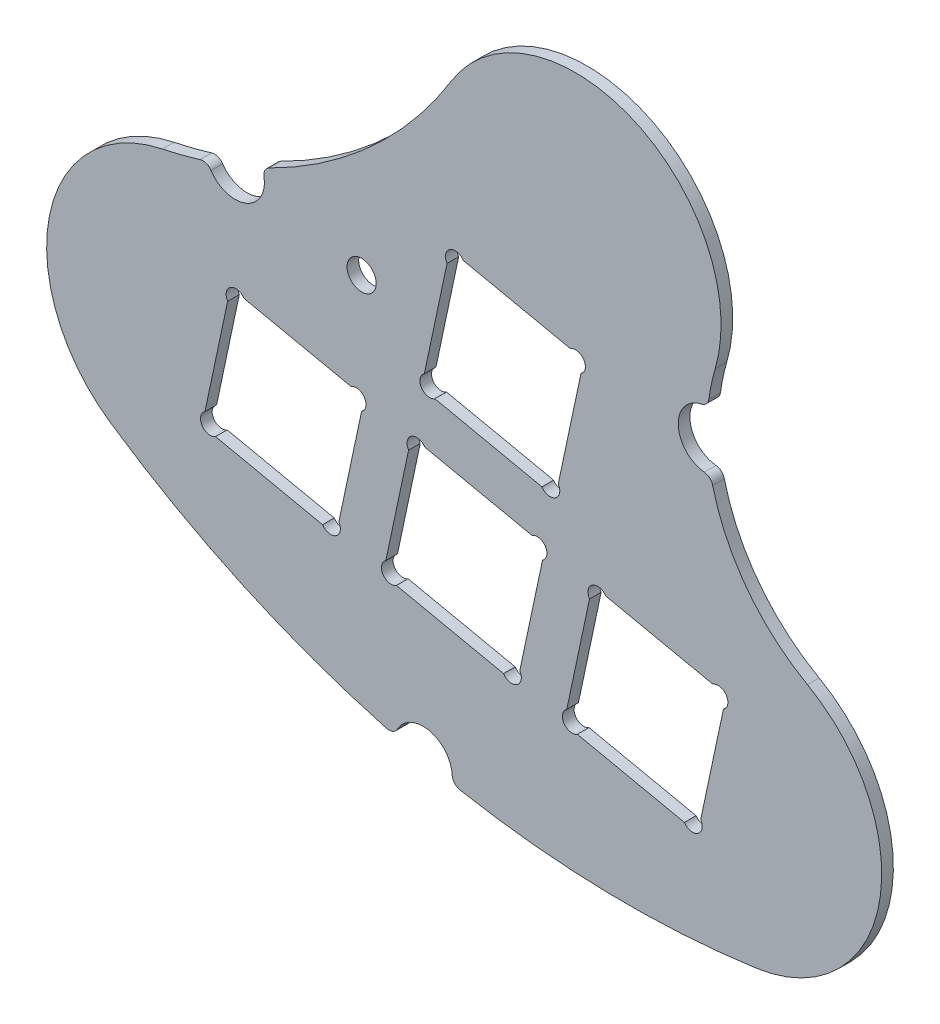
SolidWorks part; units mm, degrees
ref_plane "Front Plane" through (0, 0, 0) normal (0, 0, 1) x (1, 0, 0)
ref_plane "Top Plane" through (0, 0, 0) normal (0, 1, 0) x (1, 0, 0)
ref_plane "Right Plane" through (0, 0, 0) normal (1, 0, 0) x (0, 0, -1)
sketch "Sketch1" plane through (0, 0, 0) normal (0, 0, 1) x (1, 0, 0)
  line L0 (157.8919, 26.2701) -> (191.7747, 29.0915)
  line L1 (157.8919, 26.2701) -> (191.7747, 26.2701)
  line L2 (157.8919, 26.2701) -> (157.8919, 29.0915)
  line L3 (157.8919, 29.0915) -> (191.7747, 29.0915)
  line L4 (191.7747, 26.2701) -> (191.7747, 29.0915)
  line L5 (123.8919, 26.2701) -> (90.0092, 26.2701)
  line L6 (123.8919, 26.2701) -> (123.8919, 29.0915)
  line L7 (123.8919, 29.0915) -> (90.0092, 29.0915)
  line L8 (90.0092, 26.2701) -> (90.0092, 29.0915)
  line L9 (90.0092, 29.0915) -> (123.8919, 26.2701)
  line L10 (168.0919, 58.3601) -> (194.8735, 70.7292)
  line L11 (168.0919, 58.3601) -> (194.8735, 58.3601)
  line L12 (168.0919, 58.3601) -> (168.0919, 70.7292)
  line L13 (168.0919, 70.7292) -> (194.8735, 70.7292)
  line L14 (194.8735, 58.3601) -> (194.8735, 70.7292)
  line L15 (194.8735, 70.7292) -> (224.3587, 70.7292)
  line L16 (194.8735, 70.7292) -> (194.8735, 69.7923)
  line L17 (194.8735, 69.7923) -> (224.3587, 69.7923)
  line L18 (224.3587, 70.7292) -> (224.3587, 69.7923)
  line L19 (224.3587, 69.7923) -> (253.5106, 69.7923)
  line L20 (224.3587, 69.7923) -> (224.3587, 65.2742)
  line L21 (224.3587, 65.2742) -> (253.5106, 65.2742)
  line L22 (253.5106, 69.7923) -> (253.5106, 65.2742)
  line L23 (224.3587, 69.7923) -> (194.8735, 70.7292)
  line L24 (253.5106, 65.2742) -> (224.3587, 69.7923)
  line L25 (170.7502, 87.7401) -> (168.0919, 58.3601)
  line L26 (168.0919, 58.3601) -> (170.7502, 58.3601)
  line L27 (168.0919, 58.3601) -> (168.0919, 87.7401)
  line L28 (168.0919, 87.7401) -> (170.7502, 87.7401)
  line L29 (170.7502, 58.3601) -> (170.7502, 87.7401)
  line L30 (52.9966, 89.4705) -> (24.4119, 82.1791)
  line L31 (24.4119, 82.1791) -> (52.9966, 82.1791)
  line L32 (24.4119, 82.1791) -> (24.4119, 89.4705)
  line L33 (24.4119, 89.4705) -> (52.9966, 89.4705)
  line L34 (52.9966, 82.1791) -> (52.9966, 89.4705)
  line L35 (82.4966, 89.4705) -> (109.0019, 89.4705)
  line L36 (82.4966, 89.4705) -> (82.4966, 76.5201)
  line L37 (82.4966, 76.5201) -> (109.0019, 76.5201)
  line L38 (109.0019, 89.4705) -> (109.0019, 76.5201)
  line L39 (92.4554, 117.2387) -> (82.4966, 117.2387)
  line L40 (92.4554, 117.2387) -> (92.4554, 89.4705)
  line L41 (92.4554, 89.4705) -> (82.4966, 89.4705)
  line L42 (82.4966, 117.2387) -> (82.4966, 89.4705)
  line L43 (92.4554, 117.2387) -> (82.4966, 89.4705)
  line L44 (109.0019, 76.5201) -> (82.4966, 89.4705)
  circle A0 centre (123.8919, 26.2701) radius 14.25
  circle A1 centre (157.8919, 26.2701) radius 14.25
  circle A2 centre (90.0092, 29.0915) radius 14.25
  circle A3 centre (191.7747, 29.0915) radius 14.25
  circle A4 centre (82.4966, 89.4705) radius 11.25
  circle A5 centre (92.4554, 117.2387) radius 11.25
  circle A6 centre (52.9966, 89.4705) radius 11.25
  circle A7 centre (109.0019, 76.5201) radius 11.25
  circle A8 centre (24.4119, 82.1791) radius 11.25
  circle A9 centre (170.7502, 87.7401) radius 11.25
  circle A10 centre (168.0919, 58.3601) radius 11.25
  circle A11 centre (197.5318, 100.1092) radius 11.25
  circle A12 centre (194.8735, 70.7292) radius 11.25
  circle A13 centre (227.0169, 99.1723) radius 11.25
  circle A14 centre (224.3587, 69.7923) radius 11.25
  circle A15 centre (256.1689, 94.6541) radius 11.25
  circle A16 centre (253.5106, 65.2742) radius 11.25
  circle A17 centre (24.4119, 82.1791) radius 12
  circle A18 centre (52.9966, 89.4705) radius 12
  circle A19 centre (92.4554, 117.2387) radius 12
  circle A20 centre (82.4966, 89.4705) radius 12
  circle A21 centre (109.0019, 76.5201) radius 12
  circle A22 centre (168.0919, 58.3601) radius 12
  circle A23 centre (194.8735, 70.7292) radius 12
  circle A24 centre (224.3587, 69.7923) radius 12
  circle A25 centre (253.5106, 65.2742) radius 12
  circle A26 centre (256.1689, 94.6541) radius 12
  circle A27 centre (227.0169, 99.1723) radius 12
  circle A28 centre (197.5318, 100.1092) radius 12
  circle A29 centre (170.7502, 87.7401) radius 12
  circle A30 centre (191.7747, 29.0915) radius 15
  circle A31 centre (157.8919, 26.2701) radius 15
  circle A32 centre (123.8919, 26.2701) radius 15
  circle A33 centre (90.0092, 29.0915) radius 15
  circle A34 centre (173.429, 117.1182) radius 11.25
  circle A35 centre (173.429, 117.1182) radius 12
  dimension "D1" = 28.5
  dimension "D2" = 22.5
  dimension "D3" = 0.75
  dimension "D4" = 0.75
  dimension "D34" = 34
  dimension "D5" = 29.5
  dimension "D6" = 29.5
  dimension "D7" = 29.5
  dimension "D8" = 29.5
  dimension "D9" = 29.5
  dimension "D10" = 29.5
  dimension "D11" = 29.5
  dimension "D12" = 29.5
  dimension "D13" = 29.5
  dimension "D14" = 29.5
  dimension "D15" = 29.5
  dimension "D16" = 29.5
  dimension "D17" = 29.5
  dimension "D18" = 29.5
  dimension "D19" = 34
  dimension "D20" = 34
  dimension "D21" = 32.09
  dimension "D22" = 10.2
  dimension "D23" = 4.76
  dimension "D24" = 4.76
  dimension "D25" = 24.79
  dimension "D26" = 1.82
  dimension "D27" = 8.81
  dimension "D28" = 84.83
  dimension "D29" = 75.69
  dimension "D30" = 70.27
  dimension "D31" = 26.04
  dimension "D32" = 14.89
  dimension "D33" = 50.25
  dimension "D35" = 29.5
  dimension "D36" = 29.5
sketch "Sketch4" plane through (-30.2083, 20.075, 0) normal (0, 0, 1) x (0.9781, -0.2079, 0)
  line L0 (86.1706, 94.1917) -> (105.2206, 75.1417)
  line L1 (67.1206, 94.1917) -> (86.1706, 94.1917)
  line L2 (67.1206, 94.1917) -> (67.1206, 75.1417)
  line L3 (67.1206, 75.1417) -> (86.1706, 75.1417)
  line L4 (86.1706, 94.1917) -> (86.1706, 75.1417)
  line L5 (86.1706, 94.1917) -> (105.2206, 94.1917)
  line L6 (86.1706, 94.1917) -> (86.1706, 75.1417)
  line L7 (86.1706, 75.1417) -> (105.2206, 75.1417)
  line L8 (105.2206, 94.1917) -> (105.2206, 75.1417)
  line L9 (105.2206, 94.1917) -> (124.2706, 94.1917)
  line L10 (105.2206, 94.1917) -> (105.2206, 75.1417)
  line L11 (105.2206, 75.1417) -> (124.2706, 75.1417)
  line L12 (124.2706, 94.1917) -> (124.2706, 75.1417)
  line L13 (86.1706, 94.1917) -> (105.2206, 94.1917)
  line L14 (86.1706, 94.1917) -> (86.1706, 113.2417)
  line L15 (86.1706, 113.2417) -> (105.2206, 113.2417)
  line L16 (105.2206, 94.1917) -> (105.2206, 113.2417)
  line L17 (66.9585, 85.1784) -> (124.4326, 84.1551)
  point P14 (95.6956, 84.6667)
  point P15 (95.6956, 84.6667)
  dimension "D1" = 19.05
sketch "Sketch9" plane through (0, 0, 0) normal (0, 0, 1) x (1, 0, 0)
  line L1 (17.3619, 89.2291) -> (31.4619, 89.2291)
  line L2 (17.3619, 89.2291) -> (17.3619, 75.1291)
  line L3 (17.3619, 75.1291) -> (31.4619, 75.1291)
  line L4 (31.4619, 89.2291) -> (31.4619, 75.1291)
  line L5 (45.9466, 96.5205) -> (60.0466, 96.5205)
  line L6 (45.9466, 96.5205) -> (45.9466, 82.4205)
  line L7 (45.9466, 82.4205) -> (60.0466, 82.4205)
  line L8 (60.0466, 96.5205) -> (60.0466, 82.4205)
  line L9 (75.4466, 96.5205) -> (89.5466, 96.5205)
  line L10 (75.4466, 96.5205) -> (75.4466, 82.4205)
  line L11 (75.4466, 82.4205) -> (89.5466, 82.4205)
  line L12 (89.5466, 96.5205) -> (89.5466, 82.4205)
  line L13 (101.9519, 83.5701) -> (116.0519, 83.5701)
  line L14 (101.9519, 83.5701) -> (101.9519, 69.4701)
  line L15 (101.9519, 69.4701) -> (116.0519, 69.4701)
  line L16 (116.0519, 83.5701) -> (116.0519, 69.4701)
  line L17 (85.4054, 124.2887) -> (99.5054, 124.2887)
  line L18 (85.4054, 124.2887) -> (85.4054, 110.1887)
  line L19 (85.4054, 110.1887) -> (99.5054, 110.1887)
  line L20 (99.5054, 124.2887) -> (99.5054, 110.1887)
  line L21 (82.9592, 36.1415) -> (97.0592, 36.1415)
  line L22 (82.9592, 36.1415) -> (82.9592, 22.0415)
  line L23 (82.9592, 22.0415) -> (97.0592, 22.0415)
  line L24 (97.0592, 36.1415) -> (97.0592, 22.0415)
  line L25 (116.8419, 33.3201) -> (130.9419, 33.3201)
  line L26 (116.8419, 33.3201) -> (116.8419, 19.2201)
  line L27 (116.8419, 19.2201) -> (130.9419, 19.2201)
  line L28 (130.9419, 33.3201) -> (130.9419, 19.2201)
  line L29 (150.8419, 33.3201) -> (164.9419, 33.3201)
  line L30 (150.8419, 33.3201) -> (150.8419, 19.2201)
  line L31 (150.8419, 19.2201) -> (164.9419, 19.2201)
  line L32 (164.9419, 33.3201) -> (164.9419, 19.2201)
  line L33 (184.7247, 36.1415) -> (198.8247, 36.1415)
  line L34 (184.7247, 36.1415) -> (184.7247, 22.0415)
  line L35 (184.7247, 22.0415) -> (198.8247, 22.0415)
  line L36 (198.8247, 36.1415) -> (198.8247, 22.0415)
  line L37 (260.5606, 58.2242) -> (246.4606, 58.2242)
  line L38 (260.5606, 58.2242) -> (260.5606, 72.3242)
  line L39 (260.5606, 72.3242) -> (246.4606, 72.3242)
  line L40 (246.4606, 58.2242) -> (246.4606, 72.3242)
  line L41 (217.3087, 76.8423) -> (231.4087, 76.8423)
  line L42 (217.3087, 76.8423) -> (217.3087, 62.7423)
  line L43 (217.3087, 62.7423) -> (231.4087, 62.7423)
  line L44 (231.4087, 76.8423) -> (231.4087, 62.7423)
  line L45 (187.8235, 77.7792) -> (201.9235, 77.7792)
  line L46 (187.8235, 77.7792) -> (187.8235, 63.6792)
  line L47 (187.8235, 63.6792) -> (201.9235, 63.6792)
  line L48 (201.9235, 77.7792) -> (201.9235, 63.6792)
  line L49 (161.0419, 65.4101) -> (175.1419, 65.4101)
  line L50 (161.0419, 65.4101) -> (161.0419, 51.3101)
  line L51 (161.0419, 51.3101) -> (175.1419, 51.3101)
  line L52 (175.1419, 65.4101) -> (175.1419, 51.3101)
  line L53 (163.7002, 94.7901) -> (177.8002, 94.7901)
  line L54 (163.7002, 94.7901) -> (163.7002, 80.6901)
  line L55 (163.7002, 80.6901) -> (177.8002, 80.6901)
  line L56 (177.8002, 94.7901) -> (177.8002, 80.6901)
  line L57 (190.4818, 107.1592) -> (204.5818, 107.1592)
  line L58 (190.4818, 107.1592) -> (190.4818, 93.0592)
  line L59 (190.4818, 93.0592) -> (204.5818, 93.0592)
  line L60 (204.5818, 107.1592) -> (204.5818, 93.0592)
  line L61 (219.9669, 106.2223) -> (234.0669, 106.2223)
  line L62 (219.9669, 106.2223) -> (219.9669, 92.1223)
  line L63 (219.9669, 92.1223) -> (234.0669, 92.1223)
  line L64 (234.0669, 106.2223) -> (234.0669, 92.1223)
  line L65 (249.1189, 101.7041) -> (263.2189, 101.7041)
  line L66 (249.1189, 101.7041) -> (249.1189, 87.6041)
  line L67 (249.1189, 87.6041) -> (263.2189, 87.6041)
  line L68 (263.2189, 101.7041) -> (263.2189, 87.6041)
  line L69 (166.379, 124.1682) -> (180.479, 124.1682)
  line L70 (166.379, 124.1682) -> (166.379, 110.0682)
  line L71 (166.379, 110.0682) -> (180.479, 110.0682)
  line L72 (180.479, 124.1682) -> (180.479, 110.0682)
  point P72 (24.4119, 89.2291)
  point P74 (52.9966, 96.5205)
  point P76 (82.4966, 96.5205)
  point P78 (92.4554, 124.2887)
  point P80 (109.0019, 83.5701)
  point P82 (90.0092, 36.1415)
  point P84 (123.8919, 33.3201)
  point P86 (157.8919, 33.3201)
  point P88 (191.7747, 36.1415)
  point P90 (168.0919, 65.4101)
  point P92 (170.7502, 94.7901)
  point P94 (173.429, 124.1682)
  point P96 (197.5318, 107.1592)
  point P98 (227.0169, 106.2223)
  point P100 (256.1689, 101.7041)
  point P102 (194.8735, 77.7792)
  point P104 (224.3587, 76.8423)
  point P106 (253.5106, 72.3242)
  point P108 (17.3619, 82.1791)
  point P109 (45.9466, 89.4705)
  point P110 (75.4466, 89.4705)
  point P111 (101.9519, 76.5201)
  point P112 (85.4054, 117.2387)
  point P113 (82.9592, 29.0915)
  point P114 (116.8419, 26.2701)
  point P115 (150.8419, 26.2701)
  point P116 (184.7247, 29.0915)
  point P118 (161.0419, 58.3601)
  point P119 (187.8235, 70.7292)
  point P120 (217.3087, 69.7923)
  point P121 (246.4606, 65.2742)
  point P122 (163.7002, 87.7401)
  point P123 (190.4818, 100.1092)
  point P124 (219.9669, 99.1723)
  point P125 (249.1189, 94.6541)
  point P126 (166.379, 117.1182)
  dimension "D1" = 14.1
sketch "Sketch10" plane through (-22.0981, 19.3454, 0) normal (0, 0, 1) x (0.9781, -0.2079, 0)
  line L1 (61.5108, 90.7441) -> (75.6108, 90.7441)
  line L2 (61.5108, 90.7441) -> (61.5108, 76.6441)
  line L3 (61.5108, 76.6441) -> (75.6108, 76.6441)
  line L4 (75.6108, 90.7441) -> (75.6108, 76.6441)
  line L5 (80.5608, 90.7441) -> (94.6608, 90.7441)
  line L6 (80.5608, 90.7441) -> (80.5608, 76.6441)
  line L7 (80.5608, 76.6441) -> (94.6608, 76.6441)
  line L8 (94.6608, 90.7441) -> (94.6608, 76.6441)
  line L9 (99.6108, 90.7441) -> (113.7108, 90.7441)
  line L10 (99.6108, 90.7441) -> (99.6108, 76.6441)
  line L11 (99.6108, 76.6441) -> (113.7108, 76.6441)
  line L12 (113.7108, 90.7441) -> (113.7108, 76.6441)
  line L13 (80.5608, 109.7941) -> (94.6608, 109.7941)
  line L14 (80.5608, 109.7941) -> (80.5608, 95.6941)
  line L15 (80.5608, 95.6941) -> (94.6608, 95.6941)
  line L16 (94.6608, 109.7941) -> (94.6608, 95.6941)
  line L17 (50.5121, 89.6359) -> (53.4436, 75.8441) construction
  line L18 (59.0358, 93.2191) -> (78.0858, 93.2191) construction
  line L19 (78.0858, 112.2691) -> (97.1358, 112.2691) construction
  line L20 (97.1358, 93.2191) -> (116.1858, 93.2191) construction
  line L21 (78.0858, 93.2191) -> (78.0858, 112.2691) construction
  line L23 (59.0358, 93.2191) -> (59.0358, 74.1691) construction
  point P16 (75.6108, 83.6941)
  point P17 (94.6608, 83.6941)
  point P18 (113.7108, 83.6941)
  point P19 (87.6108, 90.7441)
  point P20 (87.6108, 109.7941)
  point P23 (68.5608, 90.7441)
  point P26 (68.5608, 93.2191)
  point P29 (87.6108, 112.2691)
  point P30 (106.6608, 90.7441)
  point P33 (106.6608, 93.2191)
  point P34 (80.5608, 102.7441)
  point P37 (78.0858, 102.7441)
  point P42 (59.0358, 83.6941)
  point P43 (61.5108, 83.6941)
sketch "Sketch14" plane through (0, 0, 0) normal (0, 0, 1) x (1, 0, 0)
  line L0 (165.1144, 80.6901) -> (163.7002, 82.1043)
  line L1 (163.7002, 93.3758) -> (165.1144, 94.7901)
  line L2 (177.8002, 93.3758) -> (176.386, 94.7901)
  line L3 (179.0648, 110.0682) -> (180.479, 111.4824)
  line L4 (166.379, 111.4824) -> (167.7932, 110.0682)
  line L5 (166.379, 122.754) -> (167.7932, 124.1682)
  line L6 (179.0648, 124.1682) -> (180.479, 122.754)
  line L7 (203.1676, 93.0592) -> (204.5818, 94.4734)
  line L8 (17.3619, 89.2291) -> (17.3619, 75.1291) construction
  line L9 (17.3619, 89.2291) -> (31.4619, 89.2291) construction
  line L10 (17.3619, 87.8149) -> (18.7761, 89.2291)
  line L11 (17.3619, 75.1291) -> (31.4619, 75.1291) construction
  line L12 (31.4619, 89.2291) -> (31.4619, 75.1291) construction
  line L13 (45.9466, 96.5205) -> (60.0466, 96.5205) construction
  line L14 (60.0466, 96.5205) -> (60.0466, 82.4205) construction
  line L15 (45.9466, 96.5205) -> (45.9466, 82.4205) construction
  line L16 (45.9466, 82.4205) -> (60.0466, 82.4205) construction
  line L17 (85.4054, 124.2887) -> (85.4054, 110.1887) construction
  line L18 (85.4054, 124.2887) -> (99.5054, 124.2887) construction
  line L19 (99.5054, 124.2887) -> (99.5054, 110.1887) construction
  line L20 (85.4054, 110.1887) -> (99.5054, 110.1887) construction
  line L21 (101.9519, 83.5701) -> (101.9519, 69.4701) construction
  line L22 (101.9519, 83.5701) -> (116.0519, 83.5701) construction
  line L23 (116.0519, 83.5701) -> (116.0519, 69.4701) construction
  line L24 (101.9519, 69.4701) -> (116.0519, 69.4701) construction
  line L25 (91.2712, 73.6044) -> (105.0631, 70.6729) construction
  line L26 (107.9947, 84.4647) -> (105.0631, 70.6729) construction
  line L27 (94.2028, 87.3963) -> (107.9947, 84.4647) construction
  line L28 (94.2028, 87.3963) -> (91.2712, 73.6044) construction
  line L29 (72.6375, 77.5651) -> (86.4294, 74.6336) construction
  line L30 (89.361, 88.4255) -> (86.4294, 74.6336) construction
  line L31 (75.5691, 91.357) -> (89.361, 88.4255) construction
  line L32 (75.5691, 91.357) -> (72.6375, 77.5651) construction
  line L33 (56.9354, 95.3177) -> (54.0038, 81.5259) construction
  line L34 (56.9354, 95.3177) -> (70.7273, 92.3862) construction
  line L35 (70.7273, 92.3862) -> (67.7957, 78.5943) construction
  line L36 (54.0038, 81.5259) -> (67.7957, 78.5943) construction
  line L37 (76.5983, 96.1988) -> (90.3901, 93.2673) construction
  line L38 (93.3217, 107.0592) -> (90.3901, 93.2673) construction
  line L39 (79.5298, 109.9907) -> (76.5983, 96.1988) construction
  line L40 (79.5298, 109.9907) -> (93.3217, 107.0592) construction
  line L41 (82.9592, 36.1415) -> (82.9592, 22.0415) construction
  line L42 (82.9592, 36.1415) -> (97.0592, 36.1415) construction
  line L43 (82.9592, 22.0415) -> (97.0592, 22.0415) construction
  line L44 (97.0592, 36.1415) -> (97.0592, 22.0415) construction
  line L45 (116.8419, 33.3201) -> (116.8419, 19.2201) construction
  line L46 (116.8419, 33.3201) -> (130.9419, 33.3201) construction
  line L47 (116.8419, 19.2201) -> (130.9419, 19.2201) construction
  line L48 (130.9419, 33.3201) -> (130.9419, 19.2201) construction
  line L49 (150.8419, 33.3201) -> (150.8419, 19.2201) construction
  line L50 (150.8419, 33.3201) -> (164.9419, 33.3201) construction
  line L51 (164.9419, 33.3201) -> (164.9419, 19.2201) construction
  line L52 (150.8419, 19.2201) -> (164.9419, 19.2201) construction
  line L53 (184.7247, 36.1415) -> (184.7247, 22.0415) construction
  line L54 (184.7247, 22.0415) -> (198.8247, 22.0415) construction
  line L55 (198.8247, 36.1415) -> (198.8247, 22.0415) construction
  line L56 (184.7247, 36.1415) -> (198.8247, 36.1415) construction
  line L57 (161.0419, 65.4101) -> (175.1419, 65.4101) construction
  line L58 (175.1419, 65.4101) -> (175.1419, 51.3101) construction
  line L59 (161.0419, 51.3101) -> (175.1419, 51.3101) construction
  line L60 (161.0419, 65.4101) -> (161.0419, 51.3101) construction
  line L61 (187.8235, 77.7792) -> (187.8235, 63.6792) construction
  line L62 (187.8235, 77.7792) -> (201.9235, 77.7792) construction
  line L63 (187.8235, 63.6792) -> (201.9235, 63.6792) construction
  line L64 (201.9235, 77.7792) -> (201.9235, 63.6792) construction
  line L65 (217.3087, 76.8423) -> (217.3087, 62.7423) construction
  line L66 (217.3087, 76.8423) -> (231.4087, 76.8423) construction
  line L67 (231.4087, 76.8423) -> (231.4087, 62.7423) construction
  line L68 (217.3087, 62.7423) -> (231.4087, 62.7423) construction
  line L69 (260.5606, 58.2242) -> (246.4606, 58.2242) construction
  line L70 (260.5606, 58.2242) -> (260.5606, 72.3242) construction
  line L71 (246.4606, 58.2242) -> (246.4606, 72.3242) construction
  line L72 (260.5606, 72.3242) -> (246.4606, 72.3242) construction
  line L73 (249.1189, 101.7041) -> (263.2189, 101.7041) construction
  line L74 (263.2189, 101.7041) -> (263.2189, 87.6041) construction
  line L75 (249.1189, 87.6041) -> (263.2189, 87.6041) construction
  line L76 (249.1189, 101.7041) -> (249.1189, 87.6041) construction
  line L77 (219.9669, 106.2223) -> (219.9669, 92.1223) construction
  line L78 (219.9669, 106.2223) -> (234.0669, 106.2223) construction
  line L79 (234.0669, 106.2223) -> (234.0669, 92.1223) construction
  line L80 (219.9669, 92.1223) -> (234.0669, 92.1223) construction
  line L81 (190.4818, 107.1592) -> (204.5818, 107.1592) construction
  line L82 (204.5818, 107.1592) -> (204.5818, 93.0592) construction
  line L83 (190.4818, 93.0592) -> (204.5818, 93.0592) construction
  line L84 (190.4818, 107.1592) -> (190.4818, 93.0592) construction
  line L85 (163.7002, 94.7901) -> (177.8002, 94.7901) construction
  line L86 (177.8002, 94.7901) -> (177.8002, 80.6901) construction
  line L87 (163.7002, 80.6901) -> (177.8002, 80.6901) construction
  line L88 (163.7002, 94.7901) -> (163.7002, 80.6901) construction
  line L89 (180.479, 124.1682) -> (180.479, 110.0682) construction
  line L90 (166.379, 110.0682) -> (180.479, 110.0682) construction
  line L91 (166.379, 124.1682) -> (166.379, 110.0682) construction
  line L92 (166.379, 124.1682) -> (180.479, 124.1682) construction
  line L93 (17.3619, 76.5433) -> (18.7761, 75.1291)
  line L94 (30.0477, 75.1291) -> (31.4619, 76.5433)
  line L95 (31.4619, 87.8149) -> (30.0477, 89.2291)
  line L96 (45.9466, 95.1063) -> (47.3608, 96.5205)
  line L97 (45.9466, 83.8347) -> (47.3608, 82.4205)
  line L98 (54.2979, 82.9092) -> (55.3871, 81.2318)
  line L99 (58.6323, 82.4205) -> (60.0466, 83.8347)
  line L100 (56.6413, 93.9344) -> (58.3187, 95.0237)
  line L101 (58.6323, 96.5205) -> (60.0466, 95.1063)
  line L102 (69.3439, 92.6802) -> (70.4332, 91.0029)
  line L103 (68.0897, 79.9776) -> (66.4124, 78.8883)
  line L104 (75.2751, 89.9737) -> (76.9524, 91.063)
  line L105 (72.9316, 78.9484) -> (74.0208, 77.2711)
  line L106 (85.0461, 74.9276) -> (86.7234, 76.0169)
  line L107 (89.0669, 87.0421) -> (87.9777, 88.7195)
  line L108 (89.0068, 93.5613) -> (90.6842, 94.6506)
  line L109 (76.8923, 97.5822) -> (77.9816, 95.9048)
  line L110 (91.9384, 107.3532) -> (93.0277, 105.6759)
  line L111 (79.2358, 108.6074) -> (80.9131, 109.6967)
  line L112 (85.4054, 111.6029) -> (86.8196, 110.1887)
  line L113 (98.0912, 110.1887) -> (99.5054, 111.6029)
  line L114 (98.0912, 124.2887) -> (99.5054, 122.8745)
  line L115 (85.4054, 122.8745) -> (86.8196, 124.2887)
  line L116 (93.9088, 86.013) -> (95.5861, 87.1023)
  line L117 (91.5653, 74.9877) -> (92.6546, 73.3104)
  line L118 (103.6798, 70.9669) -> (105.3572, 72.0562)
  line L119 (106.6114, 84.7588) -> (107.7006, 83.0814)
  line L120 (101.9519, 82.1559) -> (103.3662, 83.5701)
  line L121 (101.9519, 70.8843) -> (103.3662, 69.4701)
  line L122 (114.6377, 69.4701) -> (116.0519, 70.8843)
  line L123 (116.0519, 82.1559) -> (114.6377, 83.5701)
  line L124 (82.9592, 34.7272) -> (84.3734, 36.1415)
  line L125 (82.9592, 23.4557) -> (84.3734, 22.0415)
  line L126 (95.645, 22.0415) -> (97.0592, 23.4557)
  line L127 (97.0592, 34.7272) -> (95.645, 36.1415)
  line L128 (116.8419, 31.9059) -> (118.2562, 33.3201)
  line L129 (116.8419, 20.6343) -> (118.2562, 19.2201)
  line L130 (129.5277, 19.2201) -> (130.9419, 20.6343)
  line L131 (130.9419, 31.9059) -> (129.5277, 33.3201)
  line L132 (150.8419, 31.9059) -> (152.2562, 33.3201)
  line L133 (150.8419, 20.6343) -> (152.2562, 19.2201)
  line L134 (163.5277, 19.2201) -> (164.9419, 20.6343)
  line L135 (164.9419, 31.9059) -> (163.5277, 33.3201)
  line L136 (184.7247, 34.7272) -> (186.1389, 36.1415)
  line L137 (184.7247, 23.4557) -> (186.1389, 22.0415)
  line L138 (197.4105, 22.0415) -> (198.8247, 23.4557)
  line L139 (198.8247, 34.7272) -> (197.4105, 36.1415)
  line L140 (173.7277, 51.3101) -> (175.1419, 52.7243)
  line L141 (161.0419, 52.7243) -> (162.4562, 51.3101)
  line L142 (161.0419, 63.9959) -> (162.4562, 65.4101)
  line L143 (173.7277, 65.4101) -> (175.1419, 63.9959)
  line L144 (187.8235, 65.0934) -> (189.2378, 63.6792)
  line L145 (200.5093, 63.6792) -> (201.9235, 65.0934)
  line L146 (200.5093, 77.7792) -> (201.9235, 76.365)
  line L147 (187.8235, 76.365) -> (189.2378, 77.7792)
  line L148 (176.386, 80.6901) -> (177.8002, 82.1043)
  line L149 (204.5818, 105.745) -> (203.1676, 107.1592)
  line L150 (191.896, 107.1592) -> (190.4818, 105.745)
  line L151 (190.4818, 94.4734) -> (191.896, 93.0592)
  line L152 (219.9669, 104.8081) -> (221.3812, 106.2223)
  line L153 (232.6527, 106.2223) -> (234.0669, 104.8081)
  line L154 (234.0669, 93.5365) -> (232.6527, 92.1223)
  line L155 (219.9669, 93.5365) -> (221.3812, 92.1223)
  line L156 (229.9944, 76.8423) -> (231.4087, 75.4281)
  line L157 (217.3087, 75.4281) -> (218.7229, 76.8423)
  line L158 (217.3087, 64.1565) -> (218.7229, 62.7423)
  line L159 (229.9944, 62.7423) -> (231.4087, 64.1565)
  line L160 (259.1464, 72.3242) -> (260.5606, 70.9099)
  line L161 (246.4606, 70.9099) -> (247.8748, 72.3242)
  line L162 (259.1464, 58.2242) -> (260.5606, 59.6384)
  line L163 (247.8748, 58.2242) -> (246.4606, 59.6384)
  line L164 (261.8047, 87.6041) -> (263.2189, 89.0183)
  line L165 (249.1189, 89.0183) -> (250.5331, 87.6041)
  line L166 (249.1189, 100.2899) -> (250.5331, 101.7041)
  line L167 (261.8047, 101.7041) -> (263.2189, 100.2899)
  line L168 (75.4466, 96.5205) -> (75.4466, 82.4205) construction
  line L169 (75.4466, 96.5205) -> (89.5466, 96.5205) construction
  line L170 (89.5466, 96.5205) -> (89.5466, 82.4205) construction
  line L171 (75.4466, 82.4205) -> (89.5466, 82.4205) construction
  line L172 (76.8608, 96.5205) -> (75.4466, 95.1063)
  line L173 (88.1323, 96.5205) -> (89.5466, 95.1063)
  line L174 (89.5466, 83.8347) -> (88.1323, 82.4205)
  line L175 (75.4466, 83.8347) -> (76.8608, 82.4205)
  arc A0 (17.3619, 87.8149) -> (18.7761, 89.2291) centre (18.069, 88.522) cw
  arc A1 (18.7761, 75.1291) -> (17.3619, 76.5433) centre (18.069, 75.8362) cw
  arc A2 (31.4619, 76.5433) -> (30.0477, 75.1291) centre (30.7548, 75.8362) cw
  arc A3 (30.0477, 89.2291) -> (31.4619, 87.8149) centre (30.7548, 88.522) cw
  arc A4 (58.6323, 96.5205) -> (60.0466, 95.1063) centre (59.3394, 95.8134) cw
  arc A5 (45.9466, 95.1063) -> (47.3608, 96.5205) centre (46.6537, 95.8134) cw
  arc A6 (47.3608, 82.4205) -> (45.9466, 83.8347) centre (46.6537, 83.1276) cw
  arc A7 (60.0466, 83.8347) -> (58.6323, 82.4205) centre (59.3394, 83.1276) cw
  arc A8 (85.4054, 122.8745) -> (86.8196, 124.2887) centre (86.1125, 123.5816) cw
  arc A9 (98.0912, 124.2887) -> (99.5054, 122.8745) centre (98.7983, 123.5816) cw
  arc A10 (99.5054, 111.6029) -> (98.0912, 110.1887) centre (98.7983, 110.8958) cw
  arc A11 (85.4054, 111.6029) -> (86.8196, 110.1887) centre (86.1125, 110.8958) ccw
  arc A12 (101.9519, 82.1559) -> (103.3662, 83.5701) centre (102.6591, 82.863) cw
  arc A13 (114.6377, 83.5701) -> (116.0519, 82.1559) centre (115.3448, 82.863) cw
  arc A14 (116.0519, 70.8843) -> (114.6377, 69.4701) centre (115.3448, 70.1772) cw
  arc A15 (101.9519, 70.8843) -> (103.3662, 69.4701) centre (102.6591, 70.1772) ccw
  arc A16 (103.6798, 70.9669) -> (105.3572, 72.0562) centre (104.5185, 71.5115) ccw
  arc A17 (106.6114, 84.7588) -> (107.7006, 83.0814) centre (107.156, 83.9201) cw
  arc A18 (93.9088, 86.013) -> (95.5861, 87.1023) centre (94.7474, 86.5576) cw
  arc A19 (91.5653, 74.9877) -> (92.6546, 73.3104) centre (92.1099, 74.1491) ccw
  arc A20 (85.0461, 74.9276) -> (86.7234, 76.0169) centre (85.8848, 75.4722) ccw
  arc A21 (87.9777, 88.7195) -> (89.0669, 87.0421) centre (88.5223, 87.8808) cw
  arc A22 (75.2751, 89.9737) -> (76.9524, 91.063) centre (76.1137, 90.5183) cw
  arc A23 (72.9316, 78.9484) -> (74.0208, 77.2711) centre (73.4762, 78.1098) ccw
  arc A24 (56.6413, 93.9344) -> (58.3187, 95.0237) centre (57.48, 94.4791) cw
  arc A25 (69.3439, 92.6802) -> (70.4332, 91.0029) centre (69.8886, 91.8415) cw
  arc A26 (68.0897, 79.9776) -> (66.4124, 78.8883) centre (67.2511, 79.433) cw
  arc A27 (54.2979, 82.9092) -> (55.3871, 81.2318) centre (54.8425, 82.0705) ccw
  arc A28 (89.0068, 93.5613) -> (90.6842, 94.6506) centre (89.8455, 94.106) ccw
  arc A29 (76.8923, 97.5822) -> (77.9816, 95.9048) centre (77.4369, 96.7435) ccw
  arc A30 (79.2358, 108.6074) -> (80.9131, 109.6967) centre (80.0744, 109.1521) cw
  arc A31 (91.9384, 107.3532) -> (93.0277, 105.6759) centre (92.483, 106.5145) cw
  arc A32 (82.9592, 34.7272) -> (84.3734, 36.1415) centre (83.6663, 35.4344) cw
  arc A33 (82.9592, 23.4557) -> (84.3734, 22.0415) centre (83.6663, 22.7486) ccw
  arc A34 (95.645, 22.0415) -> (97.0592, 23.4557) centre (96.3521, 22.7486) ccw
  arc A35 (95.645, 36.1415) -> (97.0592, 34.7272) centre (96.3521, 35.4344) cw
  arc A36 (116.8419, 31.9059) -> (118.2562, 33.3201) centre (117.5491, 32.613) cw
  arc A37 (116.8419, 20.6343) -> (118.2562, 19.2201) centre (117.5491, 19.9272) ccw
  arc A38 (129.5277, 19.2201) -> (130.9419, 20.6343) centre (130.2348, 19.9272) ccw
  arc A39 (129.5277, 33.3201) -> (130.9419, 31.9059) centre (130.2348, 32.613) cw
  arc A40 (150.8419, 31.9059) -> (152.2562, 33.3201) centre (151.5491, 32.613) cw
  arc A41 (163.5277, 33.3201) -> (164.9419, 31.9059) centre (164.2348, 32.613) cw
  arc A42 (164.9419, 20.6343) -> (163.5277, 19.2201) centre (164.2348, 19.9272) cw
  arc A43 (150.8419, 20.6343) -> (152.2562, 19.2201) centre (151.5491, 19.9272) ccw
  arc A44 (184.7247, 23.4557) -> (186.1389, 22.0415) centre (185.4318, 22.7486) ccw
  arc A45 (197.4105, 22.0415) -> (198.8247, 23.4557) centre (198.1176, 22.7486) ccw
  arc A46 (197.4105, 36.1415) -> (198.8247, 34.7272) centre (198.1176, 35.4344) cw
  arc A47 (184.7247, 34.7272) -> (186.1389, 36.1415) centre (185.4318, 35.4344) cw
  arc A48 (173.7277, 65.4101) -> (175.1419, 63.9959) centre (174.4348, 64.703) cw
  arc A49 (175.1419, 52.7243) -> (173.7277, 51.3101) centre (174.4348, 52.0172) cw
  arc A50 (161.0419, 52.7243) -> (162.4562, 51.3101) centre (161.7491, 52.0172) ccw
  arc A51 (161.0419, 63.9959) -> (162.4562, 65.4101) centre (161.7491, 64.703) cw
  arc A52 (187.8235, 76.365) -> (189.2378, 77.7792) centre (188.5306, 77.0721) cw
  arc A53 (187.8235, 65.0934) -> (189.2378, 63.6792) centre (188.5306, 64.3863) ccw
  arc A54 (200.5093, 63.6792) -> (201.9235, 65.0934) centre (201.2164, 64.3863) ccw
  arc A55 (200.5093, 77.7792) -> (201.9235, 76.365) centre (201.2164, 77.0721) cw
  arc A56 (217.3087, 75.4281) -> (218.7229, 76.8423) centre (218.0158, 76.1352) cw
  arc A57 (229.9944, 76.8423) -> (231.4087, 75.4281) centre (230.7016, 76.1352) cw
  arc A58 (231.4087, 64.1565) -> (229.9944, 62.7423) centre (230.7016, 63.4494) cw
  arc A59 (217.3087, 64.1565) -> (218.7229, 62.7423) centre (218.0158, 63.4494) ccw
  arc A60 (259.1464, 58.2242) -> (260.5606, 59.6384) centre (259.8535, 58.9313) ccw
  arc A61 (246.4606, 59.6384) -> (247.8748, 58.2242) centre (247.1677, 58.9313) ccw
  arc A62 (246.4606, 70.9099) -> (247.8748, 72.3242) centre (247.1677, 71.617) cw
  arc A63 (259.1464, 72.3242) -> (260.5606, 70.9099) centre (259.8535, 71.617) cw
  arc A64 (261.8047, 101.7041) -> (263.2189, 100.2899) centre (262.5118, 100.997) cw
  arc A65 (263.2189, 89.0183) -> (261.8047, 87.6041) centre (262.5118, 88.3112) cw
  arc A66 (250.5331, 87.6041) -> (249.1189, 89.0183) centre (249.826, 88.3112) cw
  arc A67 (249.1189, 100.2899) -> (250.5331, 101.7041) centre (249.826, 100.997) cw
  arc A68 (219.9669, 104.8081) -> (221.3812, 106.2223) centre (220.674, 105.5152) cw
  arc A69 (232.6527, 106.2223) -> (234.0669, 104.8081) centre (233.3598, 105.5152) cw
  arc A70 (234.0669, 93.5365) -> (232.6527, 92.1223) centre (233.3598, 92.8294) cw
  arc A71 (221.3812, 92.1223) -> (219.9669, 93.5365) centre (220.674, 92.8294) cw
  arc A72 (203.1676, 107.1592) -> (204.5818, 105.745) centre (203.8747, 106.4521) cw
  arc A73 (204.5818, 94.4734) -> (203.1676, 93.0592) centre (203.8747, 93.7663) cw
  arc A74 (191.896, 93.0592) -> (190.4818, 94.4734) centre (191.1889, 93.7663) cw
  arc A75 (190.4818, 105.745) -> (191.896, 107.1592) centre (191.1889, 106.4521) cw
  arc A76 (176.386, 94.7901) -> (177.8002, 93.3758) centre (177.0931, 94.0829) cw
  arc A77 (177.8002, 82.1043) -> (176.386, 80.6901) centre (177.0931, 81.3972) cw
  arc A78 (165.1144, 80.6901) -> (163.7002, 82.1043) centre (164.4073, 81.3972) cw
  arc A79 (163.7002, 93.3758) -> (165.1144, 94.7901) centre (164.4073, 94.0829) cw
  arc A80 (180.479, 111.4824) -> (179.0648, 110.0682) centre (179.7719, 110.7753) cw
  arc A81 (167.7932, 110.0682) -> (166.379, 111.4824) centre (167.0861, 110.7753) cw
  arc A82 (179.0648, 124.1682) -> (180.479, 122.754) centre (179.7719, 123.4611) cw
  arc A83 (166.379, 122.754) -> (167.7932, 124.1682) centre (167.0861, 123.4611) cw
  arc A84 (75.4466, 95.1063) -> (76.8608, 96.5205) centre (76.1537, 95.8134) cw
  arc A85 (88.1323, 96.5205) -> (89.5466, 95.1063) centre (88.8394, 95.8134) cw
  arc A86 (89.5466, 83.8347) -> (88.1323, 82.4205) centre (88.8394, 83.1276) cw
  arc A87 (76.8608, 82.4205) -> (75.4466, 83.8347) centre (76.1537, 83.1276) cw
  dimension "D1" = 45
  dimension "D2" = 1
  dimension "D71" = 45
  dimension "D3" = 45
  dimension "D4" = 45
  dimension "D5" = 45
  dimension "D6" = 45
  dimension "D7" = 45
  dimension "D8" = 45
  dimension "D9" = 45
  dimension "D10" = 45
  dimension "D11" = 45
  dimension "D12" = 45
  dimension "D13" = 45
  dimension "D14" = 45
  dimension "D15" = 45
  dimension "D16" = 45
  dimension "D17" = 45
  dimension "D18" = 45
  dimension "D19" = 45
  dimension "D20" = 45
  dimension "D21" = 45
  dimension "D22" = 45
  dimension "D23" = 45
  dimension "D24" = 45
  dimension "D25" = 45
  dimension "D26" = 45
  dimension "D27" = 45
  dimension "D28" = 45
  dimension "D29" = 45
  dimension "D30" = 45
  dimension "D31" = 45
  dimension "D32" = 45
  dimension "D33" = 45
  dimension "D34" = 45
  dimension "D35" = 45
  dimension "D36" = 45
  dimension "D37" = 45
  dimension "D38" = 45
  dimension "D39" = 45
  dimension "D40" = 45
  dimension "D41" = 45
  dimension "D42" = 45
  dimension "D43" = 45
  dimension "D44" = 45
  dimension "D45" = 45
  dimension "D46" = 45
  dimension "D47" = 45
  dimension "D48" = 45
  dimension "D49" = 45
  dimension "D50" = 45
  dimension "D51" = 45
  dimension "D52" = 45
  dimension "D53" = 45
  dimension "D54" = 45
  dimension "D55" = 45
  dimension "D56" = 45
  dimension "D57" = 45
  dimension "D58" = 45
  dimension "D59" = 45
  dimension "D60" = 45
  dimension "D61" = 45
  dimension "D62" = 45
  dimension "D63" = 45
  dimension "D64" = 45
  dimension "D65" = 45
  dimension "D66" = 45
  dimension "D67" = 45
  dimension "D68" = 45
  dimension "D69" = 45
  dimension "D70" = 45
  dimension "D72" = 45
  dimension "D73" = 45
  dimension "D74" = 45
  dimension "D75" = 45
  dimension "D76" = 45
  dimension "D77" = 45
  dimension "D78" = 45
  dimension "D79" = 45
  dimension "D80" = 45
  dimension "D81" = 45
  dimension "D82" = 45
  dimension "D83" = 45
  dimension "D84" = 45
  dimension "D85" = 45
  dimension "D86" = 45
  dimension "D87" = 45
  dimension "D88" = 45
  dimension "D89" = 45
sketch "Sketch16" plane through (0, 0, 0) normal (0, 0, 1) x (1, 0, 0)
  line L0 (81.0092, 30.6915) -> (99.0092, 30.6915)
  line L5 (17.3619, 89.2291) -> (17.3619, 75.1291) construction
  line L6 (81.0092, 30.6915) -> (81.0092, 27.4915)
  line L7 (17.3619, 75.1291) -> (31.4619, 75.1291) construction
  line L8 (15.4119, 83.7791) -> (33.4119, 83.7791)
  line L9 (15.4119, 83.7791) -> (15.4119, 80.5791)
  line L10 (15.4119, 80.5791) -> (33.4119, 80.5791)
  line L11 (33.4119, 83.7791) -> (33.4119, 80.5791)
  line L12 (81.0092, 27.4915) -> (99.0092, 27.4915)
  line L13 (99.0092, 30.6915) -> (99.0092, 27.4915)
  line L14 (114.8919, 27.8701) -> (132.8919, 27.8701)
  line L15 (114.8919, 27.8701) -> (114.8919, 24.6701)
  line L16 (114.8919, 24.6701) -> (132.8919, 24.6701)
  line L17 (132.8919, 27.8701) -> (132.8919, 24.6701)
  line L18 (148.8919, 27.8701) -> (166.8919, 27.8701)
  line L19 (148.8919, 27.8701) -> (148.8919, 24.6701)
  line L20 (148.8919, 24.6701) -> (166.8919, 24.6701)
  line L21 (166.8919, 27.8701) -> (166.8919, 24.6701)
  line L22 (182.7747, 30.6915) -> (200.7747, 30.6915)
  line L23 (182.7747, 30.6915) -> (182.7747, 27.4915)
  line L24 (182.7747, 27.4915) -> (200.7747, 27.4915)
  line L25 (200.7747, 30.6915) -> (200.7747, 27.4915)
  line L26 (43.9966, 91.0705) -> (61.9966, 91.0705)
  line L27 (43.9966, 91.0705) -> (43.9966, 87.8705)
  line L28 (43.9966, 87.8705) -> (61.9966, 87.8705)
  line L29 (61.9966, 91.0705) -> (61.9966, 87.8705)
  line L30 (73.4966, 91.0705) -> (91.4966, 91.0705)
  line L31 (73.4966, 91.0705) -> (73.4966, 87.8705)
  line L32 (73.4966, 87.8705) -> (91.4966, 87.8705)
  line L33 (91.4966, 91.0705) -> (91.4966, 87.8705)
  line L34 (100.0019, 78.1201) -> (118.0019, 78.1201)
  line L35 (100.0019, 78.1201) -> (100.0019, 74.9201)
  line L36 (100.0019, 74.9201) -> (118.0019, 74.9201)
  line L37 (118.0019, 78.1201) -> (118.0019, 74.9201)
  line L38 (83.4554, 118.8387) -> (101.4554, 118.8387)
  line L39 (83.4554, 118.8387) -> (83.4554, 115.6387)
  line L40 (83.4554, 115.6387) -> (101.4554, 115.6387)
  line L41 (101.4554, 118.8387) -> (101.4554, 115.6387)
  line L42 (164.429, 118.7182) -> (182.429, 118.7182)
  line L43 (164.429, 118.7182) -> (164.429, 115.5182)
  line L44 (164.429, 115.5182) -> (182.429, 115.5182)
  line L45 (182.429, 118.7182) -> (182.429, 115.5182)
  line L46 (161.7502, 89.3401) -> (179.7502, 89.3401)
  line L47 (161.7502, 89.3401) -> (161.7502, 86.1401)
  line L48 (161.7502, 86.1401) -> (179.7502, 86.1401)
  line L49 (179.7502, 89.3401) -> (179.7502, 86.1401)
  line L50 (188.5318, 101.7092) -> (206.5318, 101.7092)
  line L51 (188.5318, 101.7092) -> (188.5318, 98.5092)
  line L52 (188.5318, 98.5092) -> (206.5318, 98.5092)
  line L53 (206.5318, 101.7092) -> (206.5318, 98.5092)
  line L54 (159.0919, 59.9601) -> (177.0919, 59.9601)
  line L55 (159.0919, 59.9601) -> (159.0919, 56.7601)
  line L56 (159.0919, 56.7601) -> (177.0919, 56.7601)
  line L57 (177.0919, 59.9601) -> (177.0919, 56.7601)
  line L58 (185.8735, 72.3292) -> (203.8735, 72.3292)
  line L59 (185.8735, 72.3292) -> (185.8735, 69.1292)
  line L60 (185.8735, 69.1292) -> (203.8735, 69.1292)
  line L61 (203.8735, 72.3292) -> (203.8735, 69.1292)
  line L62 (218.0169, 100.7723) -> (236.0169, 100.7723)
  line L63 (218.0169, 100.7723) -> (218.0169, 97.5723)
  line L64 (218.0169, 97.5723) -> (236.0169, 97.5723)
  line L65 (236.0169, 100.7723) -> (236.0169, 97.5723)
  line L66 (215.3587, 71.3923) -> (233.3587, 71.3923)
  line L67 (215.3587, 71.3923) -> (215.3587, 68.1923)
  line L68 (215.3587, 68.1923) -> (233.3587, 68.1923)
  line L69 (233.3587, 71.3923) -> (233.3587, 68.1923)
  line L70 (247.1689, 96.2541) -> (265.1689, 96.2541)
  line L71 (247.1689, 96.2541) -> (247.1689, 93.0541)
  line L72 (247.1689, 93.0541) -> (265.1689, 93.0541)
  line L73 (265.1689, 96.2541) -> (265.1689, 93.0541)
  line L74 (244.5106, 66.8742) -> (262.5106, 66.8742)
  line L75 (244.5106, 66.8742) -> (244.5106, 63.6742)
  line L76 (244.5106, 63.6742) -> (262.5106, 63.6742)
  line L77 (262.5106, 66.8742) -> (262.5106, 63.6742)
  circle A0 centre (15.4119, 82.1791) radius 1.6
  circle A1 centre (33.4119, 82.1791) radius 1.6
  circle A2 centre (81.0092, 29.0915) radius 1.6
  circle A3 centre (99.0092, 29.0915) radius 1.6
  circle A4 centre (114.8919, 26.2701) radius 1.6
  circle A5 centre (132.8919, 26.2701) radius 1.6
  circle A6 centre (148.8919, 26.2701) radius 1.6
  circle A7 centre (166.8919, 26.2701) radius 1.6
  circle A8 centre (182.7747, 29.0915) radius 1.6
  circle A9 centre (200.7747, 29.0915) radius 1.6
  circle A10 centre (43.9966, 89.4705) radius 1.6
  circle A11 centre (61.9966, 89.4705) radius 1.6
  circle A12 centre (73.4966, 89.4705) radius 1.6
  circle A13 centre (91.4966, 89.4705) radius 1.6
  circle A14 centre (100.0019, 76.5201) radius 1.6
  circle A15 centre (118.0019, 76.5201) radius 1.6
  circle A16 centre (83.4554, 117.2387) radius 1.6
  circle A17 centre (101.4554, 117.2387) radius 1.6
  circle A18 centre (164.429, 117.1182) radius 1.6
  circle A19 centre (182.429, 117.1182) radius 1.6
  circle A20 centre (161.7502, 87.7401) radius 1.6
  circle A21 centre (179.7502, 87.7401) radius 1.6
  circle A22 centre (188.5318, 100.1092) radius 1.6
  circle A23 centre (206.5318, 100.1092) radius 1.6
  circle A24 centre (159.0919, 58.3601) radius 1.6
  circle A25 centre (177.0919, 58.3601) radius 1.6
  circle A26 centre (185.8735, 70.7292) radius 1.6
  circle A27 centre (203.8735, 70.7292) radius 1.6
  circle A28 centre (218.0169, 99.1723) radius 1.6
  circle A29 centre (236.0169, 99.1723) radius 1.6
  circle A30 centre (215.3587, 69.7923) radius 1.6
  circle A31 centre (233.3587, 69.7923) radius 1.6
  circle A32 centre (247.1689, 94.6541) radius 1.6
  circle A33 centre (265.1689, 94.6541) radius 1.6
  circle A34 centre (244.5106, 65.2742) radius 1.6
  circle A35 centre (262.5106, 65.2742) radius 1.6
  point P2 (24.4119, 75.1291)
  point P6 (17.3619, 82.1791)
  point P14 (24.4119, 80.5791)
  point P53 (90.0092, 30.6915)
  point P57 (123.8919, 27.8701)
  point P60 (157.8919, 27.8701)
  point P63 (191.7747, 30.6915)
  point P73 (52.9966, 91.0705)
  point P83 (82.4966, 91.0705)
  point P93 (109.0019, 78.1201)
  point P103 (92.4554, 118.8387)
  point P113 (173.429, 118.7182)
  point P123 (170.7502, 89.3401)
  point P133 (197.5318, 101.7092)
  point P143 (168.0919, 59.9601)
  point P153 (194.8735, 72.3292)
  point P163 (227.0169, 100.7723)
  point P173 (224.3587, 71.3923)
  point P183 (256.1689, 96.2541)
  point P193 (253.5106, 66.8742)
  dimension "D1" = 3.2
  dimension "D2" = 18
sketch "Sketch8" plane through (0, 0, 0) normal (0, 0, 1) x (1, 0, 0)
  line L0 (52.2844, 74.6389) -> (82.4966, 89.4705)
  line L1 (86.9403, 110.9459) -> (79.0189, 73.6784)
  line L2 (77.6235, 112.9262) -> (96.2572, 108.9655) construction
  line L3 (69.702, 75.6588) -> (88.3357, 71.6981) construction
  line L4 (53.3861, 72.3947) -> (55.5425, 73.4534)
  line L5 (99.6829, 63.2465) -> (101.1557, 61.3487)
  line L6 (103.1308, 62.8814) -> (82.4966, 89.4705)
  line L8 (73.6628, 94.2925) -> (77.6235, 112.9262) construction
  line L9 (55.029, 98.2532) -> (73.6628, 94.2925) construction
  line L13 (93.9017, 130.158) -> (94.0202, 130.4883)
  line L14 (99.5495, 128.1325) -> (99.6679, 128.4628)
  line L16 (99.4417, 62.7418) -> (100.7607, 61.0421)
  line L17 (55.5377, 72.894) -> (53.6064, 71.9459)
  line L19 (82.4966, 89.4705) -> (96.8441, 129.4755)
  circle A1 centre (57.4203, 106.4022) radius 2.5
  circle A2 centre (106.0456, 106.2134) radius 2.5
  circle A3 centre (76.7673, 63.0854) radius 2.5
  circle A4 centre (52.9966, 89.4705) radius 13
  circle A6 centre (92.4554, 117.2387) radius 13
  circle A7 centre (109.0019, 76.5201) radius 13
  circle A8 centre (82.4966, 89.4705) radius 25
  arc A10 (50.3337, 102.1949) -> (81.377, 124.0408) centre (40.5107, 149.1329) ccw
  circle A11 centre (103.1308, 62.8814) radius 2.5
  circle A12 centre (52.2844, 74.6389) radius 2.5
  circle A13 centre (96.8441, 129.4755) radius 2.5
  circle A14 centre (52.2844, 74.6389) radius 3
  circle A15 centre (103.1308, 62.8814) radius 3
  circle A16 centre (96.8441, 129.4755) radius 3
  arc A17 (104.9258, 113.5659) -> (115.3756, 87.8504) centre (126.3001, 107.2707) ccw
  arc A18 (45.7038, 78.7088) -> (110.8301, 63.6492) centre (97.7768, 155.5511) ccw
  circle A19 centre (92.4554, 117.2387) radius 15
  circle A20 centre (109.0019, 76.5201) radius 15
  circle A21 centre (52.9966, 89.4705) radius 15
  circle A22 centre (82.4966, 89.4705) radius 27
  arc A23 (44.5818, 77.0531) -> (111.1113, 61.6691) centre (97.7768, 155.5511) ccw
  arc A24 (49.924, 104.1525) -> (79.6727, 125.0873) centre (40.5107, 149.1329) ccw
  arc A25 (106.8443, 113.0008) -> (116.3562, 89.5935) centre (126.3001, 107.2707) ccw
  circle A26 centre (52.9966, 89.4705) radius 12.5
  circle A27 centre (109.0019, 76.5201) radius 12.5
  circle A28 centre (92.4554, 117.2387) radius 12.5
  circle A29 centre (82.4966, 89.4705) radius 24.5
  arc A30 (104.4462, 113.7071) -> (115.1305, 87.4146) centre (126.3001, 107.2707) ccw
  arc A31 (110.7597, 64.1443) -> (45.9842, 79.1227) centre (97.7768, 155.5511) cw
  arc A32 (50.4361, 101.7055) -> (81.8031, 123.7792) centre (40.5107, 149.1329) ccw
  circle A33 centre (52.9966, 89.4705) radius 15.5
  circle A34 centre (109.0019, 76.5201) radius 15.5
  circle A35 centre (92.4554, 117.2387) radius 15.5
  circle A36 centre (82.4966, 89.4705) radius 27.5
  arc A37 (107.3239, 112.8596) -> (116.6013, 90.0293) centre (126.3001, 107.2707) ccw
  arc A38 (111.1816, 61.1741) -> (44.3013, 76.6392) centre (97.7768, 155.5511) cw
  arc A39 (49.8216, 104.6419) -> (79.2466, 125.349) centre (40.5107, 149.1329) ccw
  circle A40 centre (106.0456, 106.2134) radius 3
  circle A41 centre (76.7673, 63.0854) radius 3
  circle A42 centre (57.4203, 106.4022) radius 3
  circle A43 centre (70.4353, 103.1572) radius 2.5
  dimension "D3" = 26
  dimension "D4" = 5
  dimension "D7" = 6
  dimension "D8" = 50
  dimension "D1" = 2
  dimension "D2" = 2
  dimension "D5" = 0.5
  dimension "D6" = 0.5
  dimension "D9" = 0.5
  dimension "D10" = 0.5
  dimension "D11" = 5
  dimension "D12" = 8
sketch "Sketch2" plane through (0, 0, 0) normal (0, 0, 1) x (1, 0, 0)
  line L0 (30.4119, 134.2387) -> (8.4119, 112.2387)
  line L1 (16.4119, 134.2387) -> (264.1689, 134.2387)
  line L2 (8.4119, 126.2387) -> (8.4119, 15.2864)
  line L3 (16.4119, 7.2864) -> (264.1689, 7.2864)
  line L4 (272.1689, 126.2387) -> (272.1689, 15.2864)
  line L5 (16.4119, 136.2387) -> (264.1689, 136.2387)
  line L6 (6.4119, 126.2387) -> (6.4119, 15.2864)
  line L7 (16.4119, 5.2864) -> (264.1689, 5.2864)
  line L8 (274.1689, 126.2387) -> (274.1689, 15.2864)
  line L9 (250.1689, 134.2387) -> (272.1689, 112.2387)
  line L10 (6.4119, 110.2387) -> (32.4119, 136.2387)
  line L11 (248.1689, 136.2387) -> (274.1689, 110.2387)
  line L12 (6.4119, 107.4103) -> (35.2403, 136.2387)
  line L13 (245.3405, 136.2387) -> (274.1689, 107.4103)
  circle A0 centre (24.4119, 82.1791) radius 12 construction
  circle A2 centre (256.1689, 94.6541) radius 12 construction
  arc A3 (264.1689, 136.2387) -> (274.1689, 126.2387) centre (264.1689, 126.2387) cw
  circle A4 centre (123.8919, 26.2701) radius 15 construction
  arc A5 (264.1689, 5.2864) -> (274.1689, 15.2864) centre (264.1689, 15.2864) ccw
  arc A6 (6.4119, 15.2864) -> (16.4119, 5.2864) centre (16.4119, 15.2864) ccw
  arc A7 (16.4119, 136.2387) -> (6.4119, 126.2387) centre (16.4119, 126.2387) ccw
  arc A8 (264.1689, 134.2387) -> (272.1689, 126.2387) centre (264.1689, 126.2387) cw
  arc A9 (264.1689, 7.2864) -> (272.1689, 15.2864) centre (264.1689, 15.2864) ccw
  arc A10 (8.4119, 15.2864) -> (16.4119, 7.2864) centre (16.4119, 15.2864) ccw
  arc A11 (16.4119, 134.2387) -> (8.4119, 126.2387) centre (16.4119, 126.2387) ccw
  circle A12 centre (92.4554, 117.2387) radius 13 construction
  point P4 (12.4119, 82.1791)
  point P5 (92.4554, 130.2387)
  point P8 (268.1689, 94.6541)
  point P14 (124.5912, 11.2864)
  point P36 (30.4119, 134.2387)
  point P39 (250.1689, 134.2387)
  dimension "D9" = 10
  dimension "D10" = 8
  dimension "D1" = 4
  dimension "D2" = 4
  dimension "D3" = 4
  dimension "D4" = 4
  dimension "D5" = 2
  dimension "D6" = 2
  dimension "D7" = 2
  dimension "D8" = 2
  dimension "D11" = 14
  dimension "D12" = 45
  dimension "D13" = 14
  dimension "D14" = 45
  dimension "D15" = 2
  dimension "D16" = 2
sketch "Sketch6" plane through (0, 0, 0) normal (0, 0, 1) x (1, 0, 0)
  line L0 (44.9119, 130.2387) -> (56.9119, 130.2387)
  line L1 (31.4119, 130.2387) -> (43.4119, 130.2387)
  line L2 (31.4119, 130.2387) -> (31.4119, 118.2387)
  line L3 (31.4119, 118.2387) -> (43.4119, 118.2387)
  line L4 (43.4119, 130.2387) -> (43.4119, 118.2387)
  line L5 (34.1619, 133.2387) -> (40.6619, 133.2387)
  line L6 (34.1619, 133.2387) -> (34.1619, 115.2387)
  line L7 (34.1619, 115.2387) -> (40.6619, 115.2387)
  line L8 (40.6619, 133.2387) -> (40.6619, 115.2387)
  line L9 (44.9119, 130.2387) -> (44.9119, 118.2387)
  line L10 (44.9119, 118.2387) -> (56.9119, 118.2387)
  line L11 (56.9119, 130.2387) -> (56.9119, 118.2387)
  line L12 (47.6619, 133.2387) -> (54.1619, 133.2387)
  line L13 (47.6619, 133.2387) -> (47.6619, 115.2387)
  line L14 (47.6619, 115.2387) -> (54.1619, 115.2387)
  line L15 (54.1619, 133.2387) -> (54.1619, 115.2387)
  line L16 (58.4119, 130.2387) -> (70.4119, 130.2387)
  line L17 (58.4119, 130.2387) -> (58.4119, 118.2387)
  line L18 (58.4119, 118.2387) -> (70.4119, 118.2387)
  line L19 (70.4119, 130.2387) -> (70.4119, 118.2387)
  line L20 (61.1619, 133.2387) -> (67.6619, 133.2387)
  line L21 (61.1619, 133.2387) -> (61.1619, 115.2387)
  line L22 (61.1619, 115.2387) -> (67.6619, 115.2387)
  line L23 (67.6619, 133.2387) -> (67.6619, 115.2387)
  line L24 (237.1689, 130.2387) -> (249.1689, 130.2387)
  line L25 (237.1689, 130.2387) -> (237.1689, 118.2387)
  line L26 (237.1689, 118.2387) -> (249.1689, 118.2387)
  line L27 (249.1689, 130.2387) -> (249.1689, 118.2387)
  line L28 (239.9189, 133.2387) -> (246.4189, 133.2387)
  line L29 (239.9189, 133.2387) -> (239.9189, 115.2387)
  line L30 (239.9189, 115.2387) -> (246.4189, 115.2387)
  line L31 (246.4189, 133.2387) -> (246.4189, 115.2387)
  line L32 (223.6689, 130.2387) -> (235.6689, 130.2387)
  line L33 (223.6689, 130.2387) -> (223.6689, 118.2387)
  line L34 (223.6689, 118.2387) -> (235.6689, 118.2387)
  line L35 (235.6689, 130.2387) -> (235.6689, 118.2387)
  line L36 (226.4189, 133.2387) -> (232.9189, 133.2387)
  line L37 (226.4189, 133.2387) -> (226.4189, 115.2387)
  line L38 (226.4189, 115.2387) -> (232.9189, 115.2387)
  line L39 (232.9189, 133.2387) -> (232.9189, 115.2387)
  line L40 (210.1689, 130.2387) -> (222.1689, 130.2387)
  line L41 (210.1689, 130.2387) -> (210.1689, 118.2387)
  line L42 (210.1689, 118.2387) -> (222.1689, 118.2387)
  line L43 (222.1689, 130.2387) -> (222.1689, 118.2387)
  line L44 (212.9189, 133.2387) -> (219.4189, 133.2387)
  line L45 (212.9189, 133.2387) -> (212.9189, 115.2387)
  line L46 (212.9189, 115.2387) -> (219.4189, 115.2387)
  line L47 (219.4189, 133.2387) -> (219.4189, 115.2387)
  line L48 (16.4119, 134.2387) -> (264.1689, 134.2387) construction
  line L49 (8.4119, 126.2387) -> (8.4119, 15.2864) construction
  line L50 (272.1689, 126.2387) -> (272.1689, 15.2864) construction
  circle A0 centre (37.4119, 124.2387) radius 3.4
  circle A1 centre (50.9119, 124.2387) radius 3.4
  circle A2 centre (64.4119, 124.2387) radius 3.4
  circle A3 centre (243.1689, 124.2387) radius 3.4
  circle A4 centre (229.6689, 124.2387) radius 3.4
  circle A5 centre (216.1689, 124.2387) radius 3.4
  point P8 (37.4119, 130.2387)
  point P9 (37.4119, 133.2387)
  point P10 (34.1619, 124.2387)
  point P11 (31.4119, 124.2387)
  point P15 (43.4119, 124.2387)
  point P43 (243.1689, 130.2387)
  point P44 (243.1689, 133.2387)
  point P45 (239.9189, 124.2387)
  point P46 (237.1689, 124.2387)
  point P50 (249.1689, 124.2387)
  dimension "D4" = 6.8
  dimension "D9" = 6.8
  dimension "D1" = 18
  dimension "D2" = 12
  dimension "D3" = 6.5
  dimension "D5" = 3
  dimension "D6" = 18
  dimension "D7" = 12
  dimension "D8" = 6.5
  dimension "D11" = 1
  dimension "D12" = 23
  dimension "D13" = 23
  dimension "D10" = 3
sketch "Sketch13" plane through (0, 0, 0) normal (0, 0, 1) x (1, 0, 0)
  line L1 (115.4554, 133.7387) -> (125.4554, 133.7387)
  line L2 (110.4554, 128.7387) -> (110.4554, 118.7387)
  line L3 (115.4554, 113.7387) -> (125.4554, 113.7387)
  line L4 (130.4554, 128.7387) -> (130.4554, 118.7387)
  line L5 (115.9854, 134.7387) -> (124.9254, 134.7387)
  line L6 (115.9854, 134.7387) -> (115.9854, 127.3887)
  line L7 (115.9854, 127.3887) -> (124.9254, 127.3887)
  line L8 (124.9254, 134.7387) -> (124.9254, 127.3887)
  line L9 (115.5354, 132.9887) -> (116.4354, 132.9887)
  line L10 (115.5354, 132.9887) -> (115.5354, 131.2887)
  line L11 (115.5354, 131.2887) -> (116.4354, 131.2887)
  line L12 (116.4354, 132.9887) -> (116.4354, 131.2887)
  line L13 (114.4554, 120.2387) -> (126.4554, 120.2387)
  line L14 (114.4554, 120.2387) -> (114.4554, 113.7387)
  line L15 (114.4554, 113.7387) -> (126.4554, 113.7387)
  line L16 (126.4554, 120.2387) -> (126.4554, 113.7387)
  line L19 (115.4554, 134.2387) -> (125.4554, 134.2387)
  line L20 (109.9554, 128.7387) -> (109.9554, 118.7387)
  line L21 (115.4554, 113.2387) -> (125.4554, 113.2387)
  line L22 (130.9554, 128.7387) -> (130.9554, 118.7387)
  line L23 (16.4119, 134.2387) -> (264.1689, 134.2387) construction
  arc A0 (125.4554, 134.2387) -> (130.9554, 128.7387) centre (125.4554, 128.7387) cw
  arc A1 (115.4554, 133.7387) -> (110.4554, 128.7387) centre (115.4554, 128.7387) ccw
  arc A2 (125.4554, 133.7387) -> (130.4554, 128.7387) centre (125.4554, 128.7387) cw
  arc A3 (125.4554, 113.7387) -> (130.4554, 118.7387) centre (125.4554, 118.7387) ccw
  arc A4 (110.4554, 118.7387) -> (115.4554, 113.7387) centre (115.4554, 118.7387) ccw
  circle A6 centre (112.9554, 123.7387) radius 2.5
  circle A7 centre (127.9554, 123.7387) radius 2.5
  arc A8 (125.4554, 113.2387) -> (130.9554, 118.7387) centre (125.4554, 118.7387) ccw
  arc A9 (109.9554, 118.7387) -> (115.4554, 113.2387) centre (115.4554, 118.7387) ccw
  arc A10 (115.4554, 134.2387) -> (109.9554, 128.7387) centre (115.4554, 128.7387) ccw
  circle A12 centre (92.4554, 117.2387) radius 15.5 construction
  point P9 (115.9854, 132.1387)
  point P13 (116.4354, 132.1387)
  point P14 (115.9854, 132.9887)
  point P15 (120.4554, 113.7387)
  point P16 (120.4554, 127.3887)
  point P17 (120.4554, 113.7387)
  point P34 (110.4554, 123.7387)
  point P41 (120.4554, 134.2387)
  point P42 (120.4554, 133.7387)
  point P43 (130.9554, 123.7387)
  point P44 (130.4554, 123.7387)
  point P53 (107.9554, 117.2387)
  dimension "D7" = 6.5
  dimension "D10" = 5
  dimension "D11" = 5
  dimension "D17" = 5.5
  dimension "D1" = 8.94
  dimension "D2" = 7.35
  dimension "D3" = 2.6
  dimension "D4" = 1.7
  dimension "D5" = 0.9
  dimension "D6" = 1
  dimension "D8" = 12
  dimension "D9" = 7.15
  dimension "D12" = 20
  dimension "D13" = 20
  dimension "D14" = 2
  dimension "D15" = 0.5
  dimension "D16" = 0.5
sketch "Sketch5" plane through (0, 0, 0) normal (0, 0, 1) x (1, 0, 0)
  line L0 (130.9554, 128.7387) -> (130.9554, 118.7387) construction
  line L1 (136.9554, 138.2387) -> (158.5554, 138.2387)
  line L2 (136.9554, 138.2387) -> (136.9554, 106.9387)
  line L3 (136.9554, 106.9387) -> (158.5554, 106.9387)
  line L4 (158.5554, 138.2387) -> (158.5554, 106.9387)
  line L5 (141.7554, 106.9387) -> (153.7554, 106.9387)
  line L6 (141.7554, 106.9387) -> (141.7554, 93.2387)
  line L7 (141.7554, 93.2387) -> (153.7554, 93.2387)
  line L8 (153.7554, 106.9387) -> (153.7554, 93.2387)
  line L9 (16.4119, 136.2387) -> (264.1689, 136.2387) construction
  line L11 (139.9804, 102.2387) -> (155.5304, 102.2387)
  line L12 (139.9804, 102.2387) -> (139.9804, 91.2387)
  line L13 (139.9804, 91.2387) -> (155.5304, 91.2387)
  line L14 (155.5304, 102.2387) -> (155.5304, 91.2387)
  point P8 (147.7554, 106.9387)
  point P9 (147.7554, 106.9387)
  point P18 (147.7554, 93.2387)
  point P19 (147.7554, 102.2387)
  dimension "D1" = 6
  dimension "D2" = 2
  dimension "D3" = 31.3
  dimension "D4" = 21.6
  dimension "D5" = 12
  dimension "D6" = 13.7
  dimension "D7" = 15.55
  dimension "D8" = 11
  dimension "D9" = 2
sketch "Sketch3" plane through (0, 0, 0) normal (0, 0, 1) x (1, 0, 0)
  line L0 (123.8919, 26.2701) -> (157.8919, 26.2701)
  line L1 (125.5419, 80.2945) -> (156.2419, 80.2945)
  line L2 (125.5419, 80.2945) -> (125.5419, 57.0345)
  line L3 (125.5419, 57.0345) -> (156.2419, 57.0345)
  line L4 (156.2419, 80.2945) -> (156.2419, 57.0345)
  line L5 (133.1419, 59.0345) -> (148.6419, 59.0345)
  line L6 (133.1419, 59.0345) -> (133.1419, 55.0345)
  line L7 (133.1419, 55.0345) -> (148.6419, 55.0345)
  line L8 (148.6419, 59.0345) -> (148.6419, 55.0345)
  line L9 (129.0199, 77.1945) -> (152.7639, 77.1945)
  line L10 (129.0199, 77.1945) -> (129.0199, 64.3305)
  line L11 (129.0199, 64.3305) -> (152.7639, 64.3305)
  line L12 (152.7639, 77.1945) -> (152.7639, 64.3305)
  line L13 (133.1419, 55.0345) -> (130.8952, 55.0345)
  line L14 (130.8919, 61.7345) -> (150.8919, 61.7345)
  line L15 (130.8919, 61.7345) -> (130.8919, 56.2345)
  line L16 (130.8919, 56.2345) -> (150.8919, 56.2345)
  line L17 (150.8919, 61.7345) -> (150.8919, 56.2345)
  line L18 (127.5419, 78.2945) -> (154.2419, 78.2945)
  line L19 (130.8919, 56.2345) -> (150.8919, 56.2345)
  line L23 (127.5419, 78.2945) -> (127.5419, 59.0345)
  line L24 (127.5419, 59.0345) -> (154.2419, 59.0345)
  line L25 (154.2419, 78.2945) -> (154.2419, 59.0345)
  line L26 (130.8952, 59.0345) -> (150.8887, 59.0345)
  line L27 (130.8952, 59.0345) -> (130.8952, 53.0345)
  line L28 (130.8952, 53.0345) -> (150.8887, 53.0345)
  line L29 (150.8887, 59.0345) -> (150.8887, 53.0345)
  line L30 (148.6419, 55.0345) -> (150.8887, 55.0345)
  line L31 (274.1689, 126.2387) -> (274.1689, 15.2864) construction
  point P16 (140.8919, 55.0345)
  point P17 (140.8919, 57.0345)
  point P18 (140.8919, 64.3305)
  point P19 (140.8919, 26.2701)
  point P24 (140.8919, 56.2345)
  point P31 (140.8919, 78.2945)
  point P33 (140.8919, 80.2945)
  point P35 (140.8919, 59.0345)
  point P36 (125.5419, 68.6645)
  point P37 (127.5419, 68.6645)
  point P39 (130.8952, 54.0345)
  point P41 (150.8919, 59.0345)
  point P46 (274.1689, 70.7625)
  point P47 (152.7639, 70.7625)
  dimension "D1" = 30.7
  dimension "D2" = 23.26
  dimension "D3" = 4
  dimension "D4" = 15.5
  dimension "D5" = 12.864
  dimension "D6" = 23.744
  dimension "D7" = 26.7
  dimension "D8" = 20
  dimension "D9" = 5.5
  dimension "D10" = 6
  dimension "D11" = 1
  dimension "D12" = 2.8
  dimension "D13" = 19.26
  dimension "D14" = 1.1
  dimension "D15" = 5
sketch "Sketch15" plane through (0, 0, 0) normal (0, 0, 1) x (1, 0, 0)
  line L0 (25.4223, 117.2283) -> (255.1585, 117.2283)
  line L1 (16.4119, 15.2864) -> (264.1689, 15.2864)
  line L2 (16.4119, 7.2864) -> (264.1689, 7.2864) construction
  line L4 (6.4119, 107.4103) -> (35.2403, 136.2387) construction
  line L5 (20.8261, 121.8245) -> (25.4223, 117.2283)
  circle A0 centre (25.4223, 117.2283) radius 2.5
  circle A1 centre (255.1585, 117.2283) radius 2.5
  circle A2 centre (264.1689, 15.2864) radius 2.5
  circle A3 centre (16.4119, 15.2864) radius 2.5
  point P8 (140.2904, 117.2283)
  point P9 (140.2904, 15.2864)
  point P12 (140.2904, 7.2864)
  dimension "D1" = 5
  dimension "D2" = 6.5
  dimension "D3" = 90
sketch "Sketch18" plane through (0, 0, 0) normal (0, 0, 1) x (1, 0, 0)
  line L0 (125.5419, 63.0854) -> (125.5419, 99.9387)
  line L1 (130.5419, 104.9387) -> (156.429, 104.9387)
  line L2 (161.429, 109.9387) -> (161.429, 128.7387)
  line L3 (166.429, 133.7387) -> (246.3049, 133.7387)
  line L6 (268.1689, 107.7283) -> (268.1689, 58.2742)
  line L7 (263.1689, 53.2742) -> (211.7747, 53.2742)
  line L8 (206.7747, 48.2742) -> (206.7747, 16.2701)
  line L9 (201.7747, 11.2701) -> (80.0092, 11.2701)
  line L10 (75.0092, 16.2701) -> (75.0092, 33.0854)
  line L11 (70.0092, 38.0854) -> (17.4119, 38.0854)
  line L12 (12.4119, 43.0854) -> (12.4119, 107.7283)
  line L15 (34.2758, 133.7387) -> (71.4119, 133.7387)
  line L16 (76.4119, 128.7387) -> (76.4119, 122.5671)
  line L17 (68.5834, 114.7387) -> (61.4119, 114.7387)
  line L18 (36.4119, 89.7387) -> (36.4119, 63.0854)
  line L19 (41.4119, 58.0854) -> (120.5419, 58.0854)
  line L20 (16.4119, 134.2387) -> (264.1689, 134.2387) construction
  line L21 (250.6585, 129.3851) -> (250.6585, 117.7283)
  line L24 (47.6619, 115.2387) -> (54.1619, 115.2387) construction
  line L25 (239.9189, 133.2387) -> (246.4189, 133.2387) construction
  line L26 (255.6585, 112.7283) -> (263.1689, 112.7283)
  line L27 (24.9223, 112.7283) -> (17.4119, 112.7283)
  line L29 (125.5419, 80.2945) -> (125.5419, 57.0345) construction
  line L30 (32.8616, 133.1529) -> (30.5081, 130.7994)
  line L31 (75.8261, 121.1529) -> (69.9977, 115.3245)
  line L32 (6.4119, 107.4103) -> (35.2403, 136.2387) construction
  line L33 (25.4223, 117.2283) -> (255.1585, 117.2283) construction
  line L35 (27.9119, 126.7387) -> (29.9223, 126.7387)
  line L36 (27.9119, 126.7387) -> (27.9119, 121.7387)
  line L37 (27.9119, 121.7387) -> (29.9223, 121.7387)
  line L40 (247.7191, 133.1529) -> (250.0727, 130.7994)
  line L41 (252.6689, 126.7387) -> (250.6585, 126.7387)
  line L42 (252.6689, 126.7387) -> (252.6689, 121.7387)
  line L43 (252.6689, 121.7387) -> (250.6585, 121.7387)
  line L44 (250.6585, 126.7387) -> (250.6585, 121.7387)
  line L45 (245.3405, 136.2387) -> (274.1689, 107.4103) construction
  line L46 (256.1689, 94.6541) -> (253.5106, 65.2742)
  line L47 (123.8919, 26.2701) -> (157.8919, 26.2701) construction
  line L48 (29.9223, 129.3851) -> (29.9223, 126.7387)
  line L49 (29.9223, 121.7387) -> (29.9223, 117.7283)
  line L50 (20.8261, 121.8245) -> (25.4223, 117.2283) construction
  line L51 (136.9554, 106.9387) -> (158.5554, 106.9387) construction
  line L52 (31.4119, 130.2387) -> (31.4119, 118.2387) construction
  line L53 (70.4119, 130.2387) -> (70.4119, 118.2387) construction
  line L54 (210.1689, 130.2387) -> (210.1689, 118.2387) construction
  line L55 (249.1689, 130.2387) -> (249.1689, 118.2387) construction
  circle A0 centre (73.9119, 124.2387) radius 2.5
  circle A1 centre (255.1585, 117.2283) radius 2.5 construction
  circle A2 centre (24.4119, 82.1791) radius 12 construction
  circle A3 centre (90.0092, 29.0915) radius 15 construction
  circle A4 centre (157.8919, 26.2701) radius 15 construction
  circle A5 centre (191.7747, 29.0915) radius 15 construction
  circle A6 centre (253.5106, 65.2742) radius 12 construction
  circle A7 centre (256.1689, 94.6541) radius 12 construction
  circle A8 centre (173.429, 117.1182) radius 12 construction
  circle A9 centre (76.7673, 63.0854) radius 3 construction
  arc A12 (61.4119, 114.7387) -> (36.4119, 89.7387) centre (61.4119, 89.7387) ccw
  arc A15 (268.1689, 58.2742) -> (263.1689, 53.2742) centre (263.1689, 58.2742) cw
  arc A16 (80.0092, 11.2701) -> (75.0092, 16.2701) centre (80.0092, 16.2701) cw
  arc A17 (206.7747, 16.2701) -> (201.7747, 11.2701) centre (201.7747, 16.2701) cw
  arc A18 (211.7747, 53.2742) -> (206.7747, 48.2742) centre (211.7747, 48.2742) ccw
  arc A19 (161.429, 128.7387) -> (166.429, 133.7387) centre (166.429, 128.7387) cw
  arc A20 (156.429, 104.9387) -> (161.429, 109.9387) centre (156.429, 109.9387) ccw
  arc A21 (125.5419, 99.9387) -> (130.5419, 104.9387) centre (130.5419, 99.9387) cw
  arc A22 (125.5419, 63.0854) -> (120.5419, 58.0854) centre (120.5419, 63.0854) cw
  arc A23 (75.0092, 33.0854) -> (70.0092, 38.0854) centre (70.0092, 33.0854) ccw
  arc A24 (36.4119, 63.0854) -> (41.4119, 58.0854) centre (41.4119, 63.0854) ccw
  arc A25 (17.4119, 38.0854) -> (12.4119, 43.0854) centre (17.4119, 43.0854) cw
  circle A33 centre (27.9119, 124.2387) radius 2.5
  arc A34 (29.9223, 117.7283) -> (24.9223, 112.7283) centre (24.9223, 117.7283) cw
  arc A35 (12.4119, 107.7283) -> (17.4119, 112.7283) centre (17.4119, 107.7283) cw
  arc A36 (268.1689, 107.7283) -> (263.1689, 112.7283) centre (263.1689, 107.7283) ccw
  circle A37 centre (25.4223, 117.2283) radius 2.5 construction
  circle A38 centre (17.4119, 43.0854) radius 2.5
  circle A39 centre (140.8919, 16.2701) radius 2.5
  circle A40 centre (130.5419, 99.9387) radius 2.5
  circle A41 centre (252.6689, 124.2387) radius 2.5
  circle A42 centre (206.6689, 124.2387) radius 2.5
  circle A43 centre (263.1689, 79.9641) radius 2.5
  arc A44 (250.6585, 117.7283) -> (255.6585, 112.7283) centre (255.6585, 117.7283) ccw
  arc A45 (32.8616, 133.1529) -> (34.2758, 133.7387) centre (34.2758, 131.7387) cw
  arc A46 (30.5081, 130.7994) -> (29.9223, 129.3851) centre (31.9223, 129.3851) ccw
  arc A47 (250.0727, 130.7994) -> (250.6585, 129.3851) centre (248.6585, 129.3851) cw
  arc A48 (247.7191, 133.1529) -> (246.3049, 133.7387) centre (246.3049, 131.7387) ccw
  circle A49 centre (28.9223, 120.7387) radius 1
  circle A50 centre (28.9223, 127.7387) radius 1
  circle A51 centre (251.6585, 127.7387) radius 1
  circle A52 centre (251.6585, 120.7387) radius 1
  arc A53 (75.8261, 121.1529) -> (76.4119, 122.5671) centre (74.4119, 122.5671) ccw
  arc A54 (69.9977, 115.3245) -> (68.5834, 114.7387) centre (68.5834, 116.7387) cw
  arc A55 (71.4119, 133.7387) -> (76.4119, 128.7387) centre (71.4119, 128.7387) cw
  point P5 (250.6585, 133.7387)
  point P6 (25.4223, 114.7283)
  point P16 (29.9223, 133.7387)
  point P18 (76.4119, 114.7387)
  point P52 (76.7673, 60.0854)
  point P67 (27.9223, 117.2283)
  point P110 (252.6585, 117.2283)
  point P111 (255.1585, 114.7283)
  point P134 (254.8397, 79.9641)
  point P142 (140.8919, 26.2701)
  point P162 (76.4119, 121.7387)
  point P165 (69.4119, 114.7387)
  dimension "D3" = 5
  dimension "D5" = 0.5
  dimension "D10" = 2
  dimension "D11" = 25
  dimension "D12" = 5
  dimension "D13" = 2
  dimension "D6" = 2
  dimension "D9" = 2
  dimension "D17" = 5
  dimension "D19" = 2
  dimension "D20" = 2
  dimension "D21" = 2
  dimension "D1" = 0.5
  dimension "D2" = 0.5
  dimension "D4" = 0.5
  dimension "D7" = 2
  dimension "D8" = 20
  dimension "D15" = 2
  dimension "D16" = 0.5
  dimension "D18" = 5
  dimension "D22" = 3.5
  dimension "D23" = 3.5
  dimension "D24" = 3.5
  dimension "D25" = 3.5
sketch "Sketch19" plane through (0, 0, 0) normal (0, 0, 1) x (1, 0, 0)
  line L0 (11.9119, 107.7283) -> (11.9119, 43.0854)
  line L1 (17.4119, 37.5854) -> (70.0092, 37.5854)
  line L2 (74.5092, 33.0854) -> (74.5092, 16.2701)
  line L3 (80.0092, 10.7701) -> (201.7747, 10.7701)
  line L4 (207.2747, 16.2701) -> (207.2747, 48.2742)
  line L5 (211.7747, 52.7742) -> (263.1689, 52.7742)
  line L6 (268.6689, 58.2742) -> (268.6689, 107.7283)
  line L7 (263.1689, 113.2283) -> (255.6585, 113.2283)
  line L9 (70.0092, 38.0854) -> (17.4119, 38.0854) construction
  line L12 (24.9223, 113.2283) -> (17.4119, 113.2283)
  line L13 (24.9223, 112.7283) -> (17.4119, 112.7283) construction
  line L14 (75.0092, 16.2701) -> (75.0092, 33.0854) construction
  line L15 (16.4119, 134.2387) -> (264.1689, 134.2387) construction
  line L16 (12.4119, 43.0854) -> (12.4119, 107.7283) construction
  line L17 (201.7747, 11.2701) -> (80.0092, 11.2701) construction
  line L18 (206.7747, 48.2742) -> (206.7747, 16.2701) construction
  line L19 (263.1689, 53.2742) -> (211.7747, 53.2742) construction
  line L20 (268.1689, 107.7283) -> (268.1689, 58.2742) construction
  line L21 (255.6585, 112.7283) -> (263.1689, 112.7283) construction
  line L22 (251.1585, 117.7283) -> (251.1585, 121.2387)
  line L23 (245.3405, 136.2387) -> (274.1689, 107.4103) construction
  line L24 (248.0727, 133.5065) -> (250.4262, 131.1529)
  line L25 (246.3049, 134.2387) -> (166.429, 134.2387)
  line L26 (250.6585, 129.3851) -> (250.6585, 117.7283) construction
  line L27 (251.1585, 129.3851) -> (251.1585, 127.2387)
  line L28 (251.1585, 127.2387) -> (252.6689, 127.2387)
  line L29 (251.1585, 121.2387) -> (252.6689, 121.2387)
  line L30 (252.6689, 121.7387) -> (250.6585, 121.7387) construction
  line L31 (252.6689, 126.7387) -> (250.6585, 126.7387) construction
  line L32 (160.929, 128.7387) -> (160.929, 109.9387)
  line L33 (156.429, 105.4387) -> (130.5419, 105.4387)
  line L34 (125.0419, 99.9387) -> (125.0419, 63.0854)
  line L35 (120.5419, 58.5854) -> (41.4119, 58.5854)
  line L36 (36.9119, 63.0854) -> (36.9119, 89.7387)
  line L37 (61.4119, 114.2387) -> (68.5834, 114.2387)
  line L38 (76.9119, 122.5671) -> (76.9119, 128.7387)
  line L39 (71.4119, 134.2387) -> (34.2758, 134.2387)
  line L40 (76.4119, 128.7387) -> (76.4119, 122.5671) construction
  line L41 (68.5834, 114.7387) -> (61.4119, 114.7387) construction
  line L42 (70.3512, 114.9709) -> (76.1796, 120.7994)
  line L43 (32.5081, 133.5065) -> (30.1545, 131.1529)
  line L44 (75.8261, 121.1529) -> (69.9977, 115.3245) construction
  line L45 (36.4119, 89.7387) -> (36.4119, 63.0854) construction
  line L46 (41.4119, 58.0854) -> (120.5419, 58.0854) construction
  line L47 (125.5419, 63.0854) -> (125.5419, 99.9387) construction
  line L48 (130.5419, 104.9387) -> (156.429, 104.9387) construction
  line L49 (161.429, 109.9387) -> (161.429, 128.7387) construction
  line L50 (166.429, 134.2387) -> (71.4119, 134.2387)
  line L52 (6.4119, 107.4103) -> (35.2403, 136.2387) construction
  line L53 (29.4223, 117.7283) -> (29.4223, 121.2387)
  line L54 (29.4223, 129.3851) -> (29.4223, 127.2387)
  line L55 (29.9223, 129.3851) -> (29.9223, 126.7387) construction
  line L56 (27.9119, 126.7387) -> (29.9223, 126.7387) construction
  line L57 (29.4223, 127.2387) -> (27.9119, 127.2387)
  line L58 (29.4223, 121.2387) -> (27.9119, 121.2387)
  line L59 (27.9119, 121.7387) -> (29.9223, 121.7387) construction
  line L60 (252.6689, 126.7387) -> (252.6689, 121.7387) construction
  arc A0 (252.6689, 127.2387) -> (252.6689, 121.2387) centre (252.6689, 124.2387) cw
  arc A2 (251.1585, 129.3851) -> (250.4262, 131.1529) centre (248.6585, 129.3851) ccw
  arc A3 (248.0727, 133.5065) -> (246.3049, 134.2387) centre (246.3049, 131.7387) ccw
  arc A4 (251.1585, 117.7283) -> (255.6585, 113.2283) centre (255.6585, 117.7283) ccw
  arc A7 (247.7191, 133.1529) -> (246.3049, 133.7387) centre (246.3049, 131.7387) ccw construction
  arc A8 (27.9119, 121.2387) -> (27.9119, 127.2387) centre (27.9119, 124.2387) cw
  arc A9 (76.1796, 120.7994) -> (76.9119, 122.5671) centre (74.4119, 122.5671) ccw
  arc A10 (70.3512, 114.9709) -> (68.5834, 114.2387) centre (68.5834, 116.7387) cw
  arc A11 (30.1545, 131.1529) -> (29.4223, 129.3851) centre (31.9223, 129.3851) ccw
  arc A12 (32.5081, 133.5065) -> (34.2758, 134.2387) centre (34.2758, 131.7387) cw
  arc A13 (125.0419, 63.0854) -> (120.5419, 58.5854) centre (120.5419, 63.0854) cw
  arc A14 (160.929, 109.9387) -> (156.429, 105.4387) centre (156.429, 109.9387) cw
  arc A15 (130.5419, 105.4387) -> (125.0419, 99.9387) centre (130.5419, 99.9387) ccw
  arc A16 (166.429, 134.2387) -> (160.929, 128.7387) centre (166.429, 128.7387) ccw
  arc A17 (268.6689, 107.7283) -> (263.1689, 113.2283) centre (263.1689, 107.7283) ccw
  arc A18 (263.1689, 52.7742) -> (268.6689, 58.2742) centre (263.1689, 58.2742) ccw
  arc A19 (207.2747, 48.2742) -> (211.7747, 52.7742) centre (211.7747, 48.2742) cw
  arc A20 (201.7747, 10.7701) -> (207.2747, 16.2701) centre (201.7747, 16.2701) ccw
  arc A21 (74.5092, 16.2701) -> (80.0092, 10.7701) centre (80.0092, 16.2701) ccw
  arc A22 (11.9119, 43.0854) -> (17.4119, 37.5854) centre (17.4119, 43.0854) ccw
  arc A23 (41.4119, 58.5854) -> (36.9119, 63.0854) centre (41.4119, 63.0854) cw
  arc A24 (11.9119, 107.7283) -> (17.4119, 113.2283) centre (17.4119, 107.7283) cw
  arc A25 (29.4223, 117.7283) -> (24.9223, 113.2283) centre (24.9223, 117.7283) cw
  arc A26 (36.9119, 89.7387) -> (61.4119, 114.2387) centre (61.4119, 89.7387) cw
  arc A27 (76.9119, 128.7387) -> (71.4119, 134.2387) centre (71.4119, 128.7387) ccw
  arc A28 (70.0092, 37.5854) -> (74.5092, 33.0854) centre (70.0092, 33.0854) cw
  circle A29 centre (251.9085, 120.4887) radius 0.75
  circle A30 centre (251.9085, 127.9887) radius 0.75
  circle A31 centre (28.6723, 120.4887) radius 0.75
  circle A32 centre (28.6723, 127.9887) radius 0.75
  point P13 (29.4223, 134.2387)
  point P55 (251.1585, 130.4207)
  point P58 (247.3405, 134.2387)
  point P66 (76.9119, 114.2387)
  point P122 (160.929, 134.2387)
  point P145 (76.9119, 134.2387)
  dimension "D10" = 0.5
  dimension "D13" = 1.5
  dimension "D14" = 0.5
  dimension "D24" = 0.5
  dimension "D25" = 2.5
  dimension "D26" = 4.5
  dimension "D27" = 24.5
  dimension "D28" = 5.5
  dimension "D1" = 0.5
  dimension "D2" = 0.5
  dimension "D3" = 0.5
  dimension "D4" = 0.5
  dimension "D5" = 0.5
  dimension "D6" = 0.5
  dimension "D7" = 0.5
  dimension "D8" = 0.5
  dimension "D9" = 0.5
  dimension "D11" = 0.5
  dimension "D12" = 0.5
  dimension "D15" = 0.5
  dimension "D16" = 0.5
  dimension "D17" = 0.5
  dimension "D20" = 0.5
  dimension "D18" = 0.5
  dimension "D19" = 0.5
  dimension "D21" = 0.5
  dimension "D22" = 0.5
  dimension "D23" = 0.5
sketch "Sketch22" plane through (0, 0, 0) normal (0, 0, 1) x (1, 0, 0)
  line L0 (114.4554, 120.2387) -> (126.4554, 120.2387) construction
  line L1 (125.5419, 94.8666) -> (132.0419, 94.8666)
  line L2 (125.5419, 94.8666) -> (125.5419, 82.8666)
  line L3 (125.5419, 82.8666) -> (132.0419, 82.8666)
  line L4 (132.0419, 94.8666) -> (132.0419, 82.8666)
  line L5 (108.5419, 58.0854) -> (120.5419, 58.0854)
  line L6 (108.5419, 58.0854) -> (108.5419, 51.5854)
  line L7 (108.5419, 51.5854) -> (120.5419, 51.5854)
  line L8 (120.5419, 58.0854) -> (120.5419, 51.5854)
  line L9 (126.4554, 120.2387) -> (126.4554, 113.7387) construction
  line L10 (130.5419, 97.4387) -> (130.5419, 80.2945)
  line L11 (125.5419, 80.2945) -> (156.2419, 80.2945) construction
  line L14 (125.5419, 63.0854) -> (125.5419, 99.9387) construction
  circle A0 centre (130.5419, 99.9387) radius 2.5 construction
  point P19 (130.5419, 88.8666)
  point P21 (125.5419, 88.8666)
sketch "Sketch23" plane through (-19.0974, 26.7768, 0) normal (0, 0, 1) x (0.9781, -0.2079, 0)
  line L0 (111.2025, 119.1867) -> (122.9403, 121.6816) construction
  line L1 (91.2233, 65.7762) -> (103.2233, 65.7762)
  line L2 (91.2233, 65.7762) -> (91.2233, 59.2762)
  line L3 (91.2233, 59.2762) -> (103.2233, 59.2762)
  line L4 (103.2233, 65.7762) -> (103.2233, 59.2762)
  line L5 (122.9403, 121.6816) -> (124.2917, 115.3237) construction
  line L6 (95.7458, 66.2762) -> (114.7958, 66.2762) construction
  arc A0 (52.7761, 64.7332) -> (119.2503, 63.5497) centre (87.5465, 150.2598) ccw construction
  dimension "D1" = 0.5
sketch "Sketch20" plane through (0, 0, 0) normal (0, 0, 1) x (1, 0, 0)
  line L0 (173.429, 117.1182) -> (216.1689, 124.2387)
  line L1 (192.5489, 128.5387) -> (197.0489, 128.5387)
  line L2 (192.5489, 128.5387) -> (192.5489, 119.9387)
  line L3 (192.5489, 119.9387) -> (197.0489, 119.9387)
  line L4 (197.0489, 128.5387) -> (197.0489, 119.9387)
  line L9 (193.2989, 126.7387) -> (196.2989, 126.7387)
  line L10 (193.2989, 126.7387) -> (193.2989, 121.7387)
  line L11 (193.2989, 121.7387) -> (196.2989, 121.7387)
  line L12 (196.2989, 126.7387) -> (196.2989, 121.7387)
  line L13 (201.2589, 131.9887) -> (205.9589, 131.9887)
  line L14 (201.2589, 131.9887) -> (201.2589, 129.7387)
  line L15 (201.2589, 129.7387) -> (205.9589, 129.7387)
  line L16 (205.9589, 131.9887) -> (205.9589, 129.7387)
  line L17 (202.6089, 133.2387) -> (204.6089, 133.2387)
  line L18 (202.6089, 133.2387) -> (202.6089, 131.9887)
  line L19 (202.6089, 131.9887) -> (204.6089, 131.9887)
  line L20 (204.6089, 133.2387) -> (204.6089, 131.9887)
  line L21 (197.0489, 128.5387) -> (210.1689, 128.5387)
  line L22 (210.1689, 130.2387) -> (210.1689, 118.2387) construction
  line L24 (16.4119, 134.2387) -> (264.1689, 134.2387) construction
  point P10 (197.0489, 124.2387)
  point P16 (196.2989, 124.2387)
  point P17 (194.7989, 126.7387)
  point P18 (194.7989, 128.5387)
  point P27 (203.6089, 131.9887)
  point P28 (203.6089, 131.9887)
  point P29 (194.7989, 120.6784)
  point P30 (194.7989, 121.7387)
  point P31 (203.6089, 128.5387)
  point P39 (203.6089, 129.7387)
  dimension "D1" = 8.6
  dimension "D2" = 4.5
  dimension "D3" = 1
  dimension "D5" = 3
  dimension "D6" = 5
  dimension "D7" = 4.7
  dimension "D8" = 2.25
  dimension "D9" = 2
  dimension "D10" = 3.5
sketch "Sketch21" plane through (0, 0, 0) normal (0, 0, 1) x (1, 0, 0)
  line L0 (31.4119, 130.2387) -> (43.4119, 130.2387) construction
  line L1 (31.4119, 131.2387) -> (70.4119, 131.2387)
  line L2 (30.4119, 130.2387) -> (30.4119, 118.2387)
  line L3 (31.4119, 117.2387) -> (70.4119, 117.2387)
  line L4 (71.4119, 130.2387) -> (71.4119, 118.2387)
  line L5 (210.1689, 131.2387) -> (249.1689, 131.2387)
  line L6 (209.1689, 130.2387) -> (209.1689, 118.2387)
  line L7 (210.1689, 117.2387) -> (249.1689, 117.2387)
  line L8 (250.1689, 130.2387) -> (250.1689, 118.2387)
  line L9 (70.4119, 130.2387) -> (70.4119, 118.2387) construction
  line L10 (201.2589, 129.7387) -> (205.9589, 129.7387) construction
  line L11 (192.5489, 129.5387) -> (197.0489, 129.5387)
  line L12 (191.5489, 128.5387) -> (191.5489, 119.9387)
  line L13 (192.5489, 118.9387) -> (197.0489, 118.9387)
  line L14 (198.0489, 128.5387) -> (198.0489, 119.9387)
  line L15 (201.2589, 134.2387) -> (205.9589, 134.2387)
  line L16 (200.2589, 133.2387) -> (200.2589, 129.2387)
  line L17 (201.2589, 128.2387) -> (205.9589, 128.2387)
  line L18 (206.9589, 133.2387) -> (206.9589, 129.2387)
  line L19 (192.5489, 119.9387) -> (197.0489, 119.9387) construction
  line L20 (196.2989, 126.7387) -> (196.2989, 121.7387) construction
  line L21 (192.5489, 128.5387) -> (192.5489, 119.9387) construction
  line L22 (192.5489, 128.5387) -> (197.0489, 128.5387) construction
  line L23 (201.2589, 131.9887) -> (201.2589, 129.7387) construction
  line L25 (202.6089, 133.2387) -> (204.6089, 133.2387) construction
  line L26 (41.4119, 58.0854) -> (41.4119, 38.0854)
  line L27 (42.4119, 55.5854) -> (77.9119, 55.5854)
  line L28 (41.4119, 54.5854) -> (41.4119, 41.5854)
  line L29 (42.4119, 40.5854) -> (77.9119, 40.5854)
  line L30 (78.9119, 54.5854) -> (78.9119, 41.5854)
  line L31 (70.0092, 38.0854) -> (17.4119, 38.0854) construction
  line L32 (132.0419, 94.8666) -> (132.0419, 82.8666) construction
  line L33 (108.5419, 59.0854) -> (120.5419, 59.0854)
  line L34 (107.5419, 58.0854) -> (107.5419, 51.5854)
  line L35 (108.5419, 50.5854) -> (120.5419, 50.5854)
  line L36 (121.5419, 58.0854) -> (121.5419, 51.5854)
  line L37 (125.5419, 95.8666) -> (132.0419, 95.8666)
  line L38 (124.5419, 94.8666) -> (124.5419, 82.8666)
  line L39 (125.5419, 81.8666) -> (132.0419, 81.8666)
  line L40 (133.0419, 94.8666) -> (133.0419, 82.8666)
  line L41 (125.5419, 94.8666) -> (132.0419, 94.8666) construction
  line L42 (108.5419, 58.0854) -> (108.5419, 51.5854) construction
  line L43 (108.5419, 51.5854) -> (120.5419, 51.5854) construction
  line L44 (141.7554, 93.2387) -> (153.7554, 93.2387) construction
  line L45 (137.9804, 104.9387) -> (157.5304, 104.9387)
  line L46 (137.9804, 104.9387) -> (137.9804, 90.2387)
  line L47 (138.9804, 89.2387) -> (156.5304, 89.2387)
  line L48 (157.5304, 104.9387) -> (157.5304, 90.2387)
  line L49 (135.9554, 138.2387) -> (159.5554, 138.2387)
  line L50 (135.9554, 138.2387) -> (135.9554, 105.9387)
  line L51 (136.9554, 104.9387) -> (158.5554, 104.9387)
  line L52 (159.5554, 138.2387) -> (159.5554, 105.9387)
  line L54 (130.5419, 104.9387) -> (156.429, 104.9387) construction
  line L55 (155.5304, 102.2387) -> (155.5304, 91.2387) construction
  line L56 (139.9804, 91.2387) -> (155.5304, 91.2387) construction
  line L57 (136.9554, 138.2387) -> (158.5554, 138.2387) construction
  line L58 (136.9554, 138.2387) -> (136.9554, 106.9387) construction
  line L59 (82.83, 72.3572) -> (81.4785, 65.9992)
  line L60 (82.2488, 64.8132) -> (93.9866, 62.3182)
  line L61 (95.1726, 63.0885) -> (96.524, 69.4464)
  line L62 (95.7538, 70.6325) -> (84.016, 73.1274)
  line L63 (83.8081, 72.1493) -> (95.5459, 69.6543) construction
  line L64 (83.8081, 72.1493) -> (82.4567, 65.7913) construction
  line L65 (95.5459, 69.6543) -> (94.1945, 63.2964) construction
  line L66 (82.4567, 65.7913) -> (94.1945, 63.2964) construction
  arc A0 (249.1689, 131.2387) -> (250.1689, 130.2387) centre (249.1689, 130.2387) cw
  arc A1 (249.1689, 117.2387) -> (250.1689, 118.2387) centre (249.1689, 118.2387) ccw
  arc A2 (210.1689, 131.2387) -> (209.1689, 130.2387) centre (210.1689, 130.2387) ccw
  arc A3 (209.1689, 118.2387) -> (210.1689, 117.2387) centre (210.1689, 118.2387) ccw
  arc A4 (70.4119, 131.2387) -> (71.4119, 130.2387) centre (70.4119, 130.2387) cw
  arc A5 (70.4119, 117.2387) -> (71.4119, 118.2387) centre (70.4119, 118.2387) ccw
  arc A6 (31.4119, 131.2387) -> (30.4119, 130.2387) centre (31.4119, 130.2387) ccw
  arc A7 (30.4119, 118.2387) -> (31.4119, 117.2387) centre (31.4119, 118.2387) ccw
  arc A8 (197.0489, 118.9387) -> (198.0489, 119.9387) centre (197.0489, 119.9387) ccw
  arc A9 (191.5489, 119.9387) -> (192.5489, 118.9387) centre (192.5489, 119.9387) ccw
  arc A10 (192.5489, 129.5387) -> (191.5489, 128.5387) centre (192.5489, 128.5387) ccw
  arc A11 (197.0489, 129.5387) -> (198.0489, 128.5387) centre (197.0489, 128.5387) cw
  arc A12 (201.2589, 134.2387) -> (200.2589, 133.2387) centre (201.2589, 133.2387) ccw
  arc A13 (205.9589, 134.2387) -> (206.9589, 133.2387) centre (205.9589, 133.2387) cw
  arc A14 (205.9589, 128.2387) -> (206.9589, 129.2387) centre (205.9589, 129.2387) ccw
  arc A15 (200.2589, 129.2387) -> (201.2589, 128.2387) centre (201.2589, 129.2387) ccw
  arc A16 (42.4119, 55.5854) -> (41.4119, 54.5854) centre (42.4119, 54.5854) ccw
  arc A17 (41.4119, 41.5854) -> (42.4119, 40.5854) centre (42.4119, 41.5854) ccw
  arc A18 (77.9119, 40.5854) -> (78.9119, 41.5854) centre (77.9119, 41.5854) ccw
  arc A19 (77.9119, 55.5854) -> (78.9119, 54.5854) centre (77.9119, 54.5854) cw
  arc A20 (108.5419, 59.0854) -> (107.5419, 58.0854) centre (108.5419, 58.0854) ccw
  arc A21 (107.5419, 51.5854) -> (108.5419, 50.5854) centre (108.5419, 51.5854) ccw
  arc A22 (120.5419, 50.5854) -> (121.5419, 51.5854) centre (120.5419, 51.5854) ccw
  arc A23 (120.5419, 59.0854) -> (121.5419, 58.0854) centre (120.5419, 58.0854) cw
  arc A24 (125.5419, 95.8666) -> (124.5419, 94.8666) centre (125.5419, 94.8666) ccw
  arc A25 (124.5419, 82.8666) -> (125.5419, 81.8666) centre (125.5419, 82.8666) ccw
  arc A26 (132.0419, 81.8666) -> (133.0419, 82.8666) centre (132.0419, 82.8666) ccw
  arc A27 (132.0419, 95.8666) -> (133.0419, 94.8666) centre (132.0419, 94.8666) cw
  arc A28 (135.9554, 105.9387) -> (136.9554, 104.9387) centre (136.9554, 105.9387) ccw
  arc A29 (158.5554, 104.9387) -> (159.5554, 105.9387) centre (158.5554, 105.9387) ccw
  arc A30 (156.5304, 89.2387) -> (157.5304, 90.2387) centre (156.5304, 90.2387) ccw
  arc A31 (137.9804, 90.2387) -> (138.9804, 89.2387) centre (138.9804, 90.2387) ccw
  arc A32 (93.9866, 62.3182) -> (95.1726, 63.0885) centre (94.1945, 63.2964) ccw
  arc A33 (96.524, 69.4464) -> (95.7538, 70.6325) centre (95.5459, 69.6543) ccw
  arc A34 (82.83, 72.3572) -> (84.016, 73.1274) centre (83.8081, 72.1493) cw
  arc A35 (81.4785, 65.9992) -> (82.2488, 64.8132) centre (82.4567, 65.7913) ccw
  point P8 (50.9119, 131.2387)
  point P11 (229.6689, 131.2387)
  point P12 (30.4119, 124.2387)
  point P41 (203.6089, 128.2387)
  point P44 (203.6089, 129.7387)
  point P45 (194.7989, 118.9387)
  point P48 (194.7989, 119.9387)
  point P49 (198.0489, 124.2387)
  point P52 (196.2989, 124.2387)
  point P81 (41.4119, 48.0854)
  point P82 (41.4119, 48.0854)
  point P102 (132.0419, 88.8666)
  point P103 (133.0419, 88.8666)
  point P106 (128.7919, 94.8666)
  point P107 (128.7919, 95.8666)
  point P110 (108.5419, 54.8354)
  point P111 (107.5419, 54.8354)
  point P112 (114.5419, 50.5854)
  point P115 (114.5419, 51.5854)
  point P118 (41.4119, 55.5854)
  point P123 (78.9119, 40.5854)
  point P126 (78.9119, 55.5854)
  point P151 (147.7554, 138.2387)
  point P152 (147.7554, 104.9387)
  point P155 (147.7554, 93.2387)
  dimension "D3" = 1
  dimension "D9" = 1
  dimension "D14" = 1
  dimension "D19" = 1
  dimension "D24" = 1
  dimension "D1" = 1
  dimension "D2" = 1
  dimension "D4" = 1
  dimension "D5" = 1
  dimension "D6" = 1
  dimension "D7" = 1
  dimension "D8" = 1.5
  dimension "D10" = 15
  dimension "D11" = 37.5
  dimension "D12" = 1
  dimension "D13" = 1
  dimension "D15" = 2
  dimension "D16" = 2
  dimension "D17" = 1
  dimension "D18" = 23.6
  dimension "D20" = 1
  dimension "D21" = 1
  dimension "D22" = 1
  dimension "D23" = 1
sketch "Sketch24" plane through (0, 0, 0) normal (0, 0, 1) x (1, 0, 0)
  line L0 (6.4119, 126.2387) -> (6.4119, 15.2864) construction
  line L1 (30.4223, 10.2864) -> (80.4223, 10.2864)
  line L2 (30.4223, 10.2864) -> (30.4223, 131.2387)
  line L3 (30.4223, 131.2387) -> (80.4223, 131.2387)
  line L4 (80.4223, 10.2864) -> (80.4223, 131.2387)
  line L5 (11.4119, 29.2968) -> (30.4223, 29.2968)
  line L6 (11.4119, 29.2968) -> (11.4119, 112.2283)
  line L7 (11.4119, 112.2283) -> (30.4223, 112.2283)
  line L8 (30.4223, 29.2968) -> (30.4223, 112.2283)
  line L9 (16.4119, 136.2387) -> (264.1689, 136.2387) construction
  line L10 (250.1585, 29.2968) -> (269.1689, 29.2968)
  line L11 (250.1585, 29.2968) -> (250.1585, 112.2283)
  line L12 (250.1585, 112.2283) -> (269.1689, 112.2283)
  line L13 (269.1689, 29.2968) -> (269.1689, 112.2283)
  line L14 (200.1585, 10.2864) -> (250.1585, 10.2864)
  line L15 (200.1585, 10.2864) -> (200.1585, 131.2387)
  line L16 (200.1585, 131.2387) -> (250.1585, 131.2387)
  line L17 (250.1585, 10.2864) -> (250.1585, 131.2387)
  line L18 (274.1689, 126.2387) -> (274.1689, 15.2864) construction
  point P8 (30.4223, 70.7625)
  point P9 (30.4223, 70.7625)
  point P12 (6.4119, 70.7625)
  point P23 (250.1585, 70.7625)
  point P24 (250.1585, 70.7625)
  point P28 (269.1689, 70.7625)
  point P31 (274.1689, 70.7625)
  dimension "D1" = 5
  dimension "D2" = 50
  dimension "D3" = 5
  dimension "D4" = 5
  dimension "D5" = 5
  dimension "D6" = 5
extrude "Boss-Extrude1" add sketch "Sketch8" along normal blind 1.2 contours A42 A33 A24 A21 | A42 A24 A33 | A24 A42 A33 A1 | A33 A10 A1 A24 | A33 A42 A21 A10 A1 | A10 A33 A1 | A32 A33 A1 A21 | A21 A42 A33 A32 | A1 A33 A10 | A33 A1 A10 | A36 A10 A1 A32 | A33 A42 A36 A32 | A33 A32 A1 | A36 A42 A24 A1 A10 | A42 A36 A24 | A42 A21 A36 A33 | A42 A33 A36 | A42 A10 A22 A24 A36 | A42 A36 A33 A22 A32 | A36 A42 A32 | A32 A42 A10 A36 | A42 A32 A22 A10 | A10 A42 A36 | A33 A36 A21 A22 | A10 A36 A24 A22 | A36 A10 A35 A24 | A36 A32 A35 A10 | A32 A36 A10 A22 | A35 A36 A32 A22 | A19 A36 A35 A22 | A36 A19 A32 A35 | A36 A35 A32 | A10 A35 A32 A19 | A24 A35 A10 A19 | A41 A22 A18 A36 A23 | A31 A36 A18 A22 | A33 A36 A31 A22 | A36 A33 A14 A31 | A36 A31 L4 A18 | A36 A18 L17 A14 A23 | A12 A23 A14 L4 | A33 A12 A23 A18 | A18 A12 L4 A14 | A18 L4 A14 L17 | L4 A31 A14 A18 | A18 A14 L4 | A14 A31 A12 A18 | A33 A12 A31 A14 | A33 A31 A12 | A33 A18 A12 A31 | A31 A33 A12 A21 | A18 A33 A31 A21 | A12 A33 A18 A21 | A14 A33 A12 A21 | A33 A14 A23 A12 | A33 A23 A14 | A23 A33 A14 A21 | A12 A33 A14 A21 | A36 A21 A14 A33 | A21 A36 A33 A22 | A41 A23 A36 A18 A22 | A36 A23 A15 L16 A18 | A36 A18 L5 A31 | A36 A31 A15 A34 | A31 A36 A34 A22 | A18 A36 A31 A22 | A34 A36 A20 A22 | A36 A34 A15 A20 | A15 A34 A11 A20 | A34 A15 A31 A11 | A11 A31 A15 A18 | A15 A31 L5 A18 | A18 L16 A15 L5 | A15 A23 A11 L5 | A18 A15 L5 A11 | A18 L5 A15 | A34 A18 A11 A23 | A34 A31 A11 A18 | A34 A11 A31 | A11 A34 A31 A20 | A31 A34 A18 A20 | A18 A34 A11 A20 | A11 A34 A15 A20 | A34 A11 A23 A15 | A15 A34 A23 A20 | A34 A15 A23 | A36 A17 A34 A25 | A30 A34 A22 A20 | A20 A36 A34 A30 | A34 A36 A17 A22 A30 | A36 A34 A17 | A36 A20 A17 A34 | A25 A34 A17 A20 | A17 A36 A25 A22 | A22 A35 A30 A19 | A2 A36 A19 A30 A35 | A36 A2 A17 A19 | A36 A35 A17 A2 | A35 A36 A2 | A17 A36 A35 A2 A22 | A36 A17 A35 | A2 A36 A17 A22 | A36 A2 A25 A35 A17 | A40 A22 A25 A36 | A40 A36 A25 | A36 A40 A25 A2 | A22 A40 A36 A2 | A17 A35 A2 | A35 A40 A19 A2 | A25 A40 A35 A2 | A40 A25 A35 | A40 A35 A25 A19 | A21 | A19 | A20 | A22 region at (53.5201, 74.2373, 0) region at (51.4161, 74.3218, 0) region at (54.3508, 74.3334, 0) region at (49.5389, 74.6166, 0) region at (54.215, 73.81, 0) region at (52.27, 73.3192, 0) region at (55.0152, 74.3537, 0) region at (54.6074, 74.0025, 0) region at (49.6193, 74.0889, 0) region at (47.942, 75.1751, 0) region at (54.4081, 73.054, 0) region at (54.8072, 73.5543, 0) region at (57.0921, 74.817, 0) region at (54.9828, 73.9355, 0) region at (48.9363, 74.3907, 0) region at (53.7636, 72.3583, 0) region at (54.9274, 73.172, 0) region at (55.1946, 73.4235, 0) region at (59.1024, 75.4969, 0) region at (58.8335, 72.966, 0) region at (53.4812, 104.6345, 0) region at (54.8461, 72.7401, 0) region at (59.3832, 71.347, 0) region at (61.353, 72.4149, 0) region at (60.6267, 69.3748, 0) region at (55.5219, 104.4793, 0) region at (54.2282, 105.0798, 0) region at (64.2212, 69.2698, 0) region at (68.446, 66.2924, 0) region at (55.012, 105.1338, 0) region at (59.1024, 103.4442, 0) region at (58.6807, 103.5552, 0) region at (58.2488, 103.7808, 0) region at (57.5518, 103.8766, 0) region at (57.5031, 104.0635, 0) region at (56.5134, 104.3656, 0) region at (57.8497, 105.6419, 0) region at (59.633, 104.1611, 0) region at (59.0015, 103.8226, 0) region at (58.2829, 104.0554, 0) region at (58.9213, 104.1276, 0) region at (58.5707, 104.4988, 0) region at (60.0844, 106.414, 0) region at (59.5059, 104.3689, 0) region at (59.4401, 104.7689, 0) region at (93.3244, 61.8139, 0) region at (100.8005, 61.4817, 0) region at (85.0567, 62.4749, 0) region at (61.3135, 107.5919, 0) region at (60.401, 105.2458, 0) region at (59.9169, 104.9836, 0) region at (60.2182, 105.5185, 0) region at (99.9955, 62.2999, 0) region at (102.5644, 61.6894, 0) region at (105.2839, 61.2172, 0) region at (106.03, 61.1885, 0) region at (95.3074, 63.04, 0) region at (90.0486, 63.2976, 0) region at (71.8779, 114.4767, 0) region at (74.9543, 117.6146, 0)
extrude "Cut-Extrude1" cut sketch "Sketch8<3>" along normal through all contours A42 | A40 | A41
sketch "Sketch8<3>" plane through (0, 0, 0) normal (0, 0, 1) x (1, 0, 0) same geometry as "Sketch8"
extrude "Cut-Extrude2" cut sketch "Sketch14" along normal through all contours A24 L100 | A25 L102 | A26 L103 | A27 L98 | A22 L104 | A23 L105 | A20 L106 | A21 L107 | A18 L116 | A17 L119 | A16 L118 | A19 L117 | A28 L108 | A29 L109 | A30 L111 | A31 L110
extrude "Cut-Extrude3" cut sketch "Sketch10" along normal through all
hole_wizard "Ø3.0mm Dowel Hole1" positions "Sketch25" profile "Sketch26" hole size "Ø3.0" standard "ANSI Metric" end condition through all
sketch "Sketch25" plane through (0, 0, 1.2) normal (0, 0, 1) x (1, 0, 0)
  point P0 (70.4353, 103.1572)
sketch "Sketch26" plane through (70.4353, 103.1572, 1.2) normal (1, 0, 0) x (0, -1, 0)
  line L0 (0, 0) -> (0, 1.2)
  line L1 (0, 1.2) -> (1.5, 1.2)
  line L2 (1.5, 1.2) -> (1.5, 0)
  line L5 (1.5, 0) -> (0, 0)
  line L11 (0, -6.35) -> (0, 107.95) construction
  dimension "Thru Hole Dia." = 3
  dimension "Thru Hole Depth" = 1.2
fillet "Fillet1" radius 1 6 edges at (79.7025, 62.4653, 0.6) (73.8523, 63.7946, 0.6) (106.4231, 103.2373, 0.6) (106.1112, 109.2127, 0.6) (54.5962, 105.3899, 0.6) (60.1723, 107.5965, 0.6)
